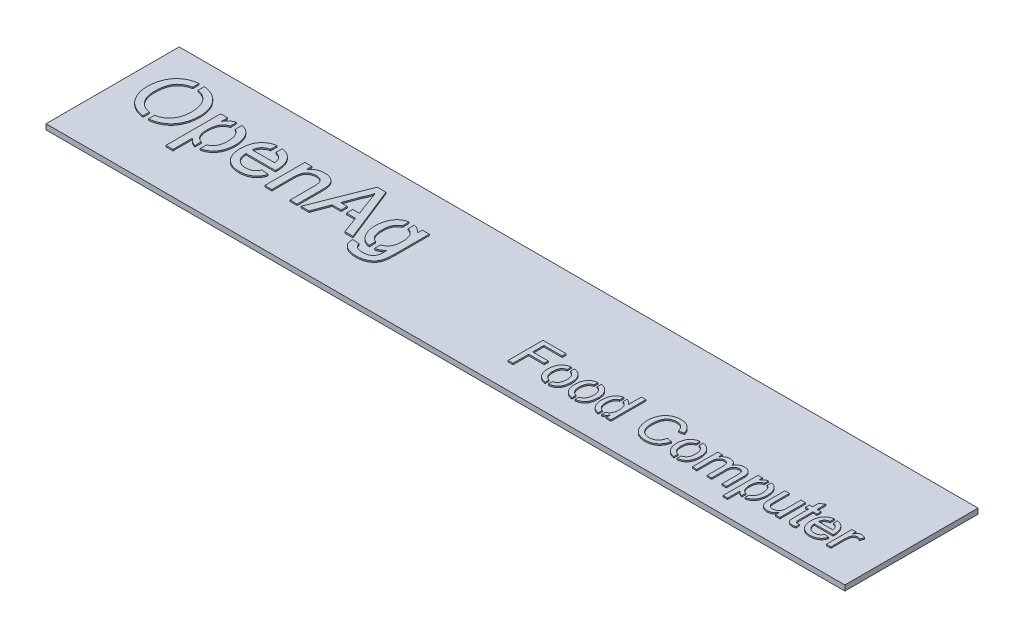
SolidWorks part; units mm, degrees
ref_plane "Front" through (0, 0, 0) normal (0, 0, 1) x (1, 0, 0)
ref_plane "Top" through (0, 0, 0) normal (0, 1, 0) x (1, 0, 0)
ref_plane "Right" through (0, 0, 0) normal (1, 0, 0) x (0, 0, -1)
sketch "Sketch1" plane through (0, 0, 0) normal (0, 1, 0) x (1, 0, 0)
  line L0 (-150, 18.65) -> (150, 18.65) construction
  line L1 (-150, 25) -> (150, 25) construction
  line L2 (-150, 25) -> (-150, -25) construction
  line L3 (-150, -25) -> (150, -25) construction
  line L4 (150, 25) -> (150, -25) construction
  line L5 (-150, 25) -> (150, -25) construction
  line L6 (-150, -25) -> (150, 25) construction
  line L7 (150, -18.65) -> (-150, -18.65) construction
  line L8 (0, 18.65) -> (0, 25) construction
  line L9 (0, -18.65) -> (0, -25) construction
  line L10 (-150, -4.4674) -> (-33.5363, -4.4674) construction
  line L11 (-33.5363, -4.4674) -> (-33.5363, 25) construction
  line L12 (150, -15.7009) -> (1.3927, -15.7009) construction
  line L13 (1.3927, -15.7009) -> (1.3927, -25) construction
  line L14 (-143.65, 25) -> (-143.65, -25) construction
  line L15 (143.65, 25) -> (143.65, -25) construction
  text T0 "OpenAg" font "Arial" height in points 80
  text T1 "Food Computer" font "Arial" height in points 51
  point P0 (0, 0)
  point P24 (1.3927, -15.7009)
  point P25 (0, 0)
  dimension "D1" = 300
  dimension "D2" = 50
  dimension "D3" = 6.35
  dimension "D4" = 6.35
  dimension "D5" = 6.35
extrude "Boss-Extrude1" add sketch "Sketch1" along normal blind 2.5
sketch "Sketch4" plane through (0, 0, 0) normal (0, 1, 0) x (1, 0, 0)
  line L1 (-150, 25) -> (150, 25)
  line L2 (-150, 25) -> (-150, -25)
  line L3 (-150, -25) -> (150, -25)
  line L4 (150, 25) -> (150, -25)
  line L5 (-150, 25) -> (150, -25) construction
  line L6 (-150, -25) -> (150, 25) construction
  point P0 (0, 0)
  dimension "D1" = 50
  dimension "D2" = 300
extrude "Boss-Extrude2" add sketch "Sketch4" along normal blind 2
sketch "Sketch5" plane through (0, 2, 0) normal (0, 1, 0) x (1, 0, 0)
  line L0 (-132.8325, 13.9718) -> (-132.8489, 16.3426) construction
  line L1 (-132.8736, -2.3601) -> (-132.8613, -4.7308) construction
  line L2 (-98.012, 8.4401) -> (-97.9996, 10.8108) construction
  line L3 (-65.0313, 4.2254) -> (-65.0313, 1.8546) construction
  line L4 (-48.2865, -2.0896) -> (-48.2673, -4.4674) construction
  line L6 (-48.3908, 10.8108) -> (-48.3715, 8.43) construction
  line L8 (-113.1461, 10.8108) -> (-113.1461, 8.4271) construction
  line L9 (28.8495, -7.4724) -> (28.8495, -5.961) construction
  line L10 (28.8495, -14.3574) -> (28.8495, -15.8688) construction
  line L11 (38.9253, -7.4724) -> (38.9253, -5.961) construction
  line L12 (38.9253, -14.3574) -> (38.9253, -15.8688) construction
  line L13 (48.5916, -5.961) -> (48.5916, -7.4762) construction
  line L14 (48.7701, -14.3574) -> (48.7701, -15.8615) construction
  line L15 (77.213, -7.4724) -> (77.213, -5.961) construction
  line L16 (77.213, -14.3574) -> (77.213, -15.8688) construction
  line L17 (102.8745, -5.961) -> (102.8745, -7.4806) construction
  line L18 (102.6777, -15.8688) -> (102.6777, -14.3556) construction
  line L19 (127.6361, -7.4724) -> (127.644, -5.961) construction
  line L20 (-113.4548, -4.7308) -> (-113.4548, -2.3572) construction
  line L21 (-68.5381, 4.2254) -> (-61.5246, 4.2254) construction
  line L22 (-69.4106, 1.8546) -> (-60.652, 1.8546) construction
  line L39 (-69.4106, 1.8546) -> (-60.652, 1.8546) construction
  line L70 (-66.0313, 1.8546) -> (-64.0313, 1.8546)
  line L83 (-66.0313, 4.2254) -> (-64.0313, 4.2254)
  line L85 (-131.832, 13.9054) -> (-131.8486, 16.3007)
  line L86 (-133.874, -2.2961) -> (-133.8615, -4.6884)
  line L87 (-114.1461, 10.7192) -> (-114.1461, 8.3626)
  line L88 (-112.4548, -4.6448) -> (-112.4548, -2.1851)
  line L89 (-97.0124, 8.3488) -> (-96.9999, 10.7492)
  line L90 (-66.0313, 4.2254) -> (-66.0313, 1.8546)
  line L91 (-49.2881, -1.897) -> (-49.2678, -4.4011)
  line L92 (-49.3902, 10.7356) -> (-49.3697, 8.2033)
  line L93 (-133.832, 13.9081) -> (-133.8487, 16.3016)
  line L94 (-131.8739, -2.2986) -> (-131.8615, -4.6854)
  line L95 (-112.1461, 10.7335) -> (-112.1461, 8.1741)
  line L96 (-114.4548, -4.6242) -> (-114.4548, -2.2397)
  line L97 (-99.0125, 8.352) -> (-98.9999, 10.7539)
  line L98 (-64.0313, 4.2254) -> (-64.0313, 1.8546)
  line L99 (-47.2871, -2.0156) -> (-47.2679, -4.3821)
  line L100 (-47.39, 10.7215) -> (-47.3709, 8.3625)
  line L101 (29.4495, -7.5363) -> (29.4495, -5.994)
  line L102 (28.2495, -14.2956) -> (28.2495, -15.8367)
  line L103 (38.3253, -14.2956) -> (38.3253, -15.8367)
  line L104 (39.5253, -7.5363) -> (39.5253, -5.994)
  line L105 (47.9916, -6.0055) -> (47.9916, -7.5875)
  line L106 (48.1701, -14.2737) -> (48.1701, -15.8438)
  line L107 (77.813, -7.5363) -> (77.813, -5.994)
  line L108 (76.613, -14.2956) -> (76.613, -15.8367)
  line L109 (102.2745, -6.0122) -> (102.2745, -7.5133)
  line L110 (103.2777, -15.8201) -> (103.2777, -14.2584)
  line L111 (128.2359, -7.5234) -> (128.2438, -5.9957)
  line L112 (28.2495, -7.5343) -> (28.2495, -5.9936)
  line L113 (29.4495, -14.2918) -> (29.4495, -15.8319)
  line L114 (39.5253, -14.2918) -> (39.5253, -15.8319)
  line L115 (38.3253, -7.5343) -> (38.3253, -5.9936)
  line L116 (49.1916, -6.0167) -> (49.1916, -7.5243)
  line L117 (49.3701, -14.2776) -> (49.3701, -15.7769)
  line L118 (76.613, -7.5343) -> (76.613, -5.9936)
  line L119 (77.813, -14.2918) -> (77.813, -15.8319)
  line L120 (103.4745, -6.0047) -> (103.4745, -7.6254)
  line L121 (102.0777, -15.8092) -> (102.0777, -14.2904)
  line L122 (127.0359, -7.5218) -> (127.0438, -5.9931)
  line L123 (-133.8324, 13.9649) -> (-133.8489, 16.3356) construction
  line L124 (-131.8325, 13.9788) -> (-131.8489, 16.3495) construction
  line L125 (-133.8736, -2.3653) -> (-133.8613, -4.736) construction
  line L126 (-131.8736, -2.3548) -> (-131.8613, -4.7256) construction
  line L127 (-114.4548, -4.7308) -> (-114.4548, -2.3572) construction
  line L128 (-112.4548, -4.7308) -> (-112.4548, -2.3572) construction
  line L129 (-112.1461, 10.8108) -> (-112.1461, 8.4271) construction
  line L130 (-114.1461, 10.8108) -> (-114.1461, 8.4271) construction
  line L131 (-99.012, 8.4453) -> (-98.9996, 10.816) construction
  line L132 (-97.012, 8.4348) -> (-96.9997, 10.8056) construction
  line L133 (-49.3907, 10.8027) -> (-49.3715, 8.4219) construction
  line L134 (-47.3908, 10.8189) -> (-47.3715, 8.4381) construction
  line L135 (-49.2865, -2.0977) -> (-49.2672, -4.4755) construction
  line L136 (-47.2865, -2.0815) -> (-47.2673, -4.4593) construction
  line L137 (28.2495, -7.4724) -> (28.2495, -5.961) construction
  line L138 (29.4495, -7.4724) -> (29.4495, -5.961) construction
  line L139 (28.2495, -14.3574) -> (28.2495, -15.8688) construction
  line L140 (29.4495, -14.3574) -> (29.4495, -15.8688) construction
  line L141 (38.3253, -14.3574) -> (38.3253, -15.8688) construction
  line L142 (39.5253, -14.3574) -> (39.5253, -15.8688) construction
  line L143 (38.3253, -7.4724) -> (38.3253, -5.961) construction
  line L144 (39.5253, -7.4724) -> (39.5253, -5.961) construction
  line L145 (47.9916, -5.961) -> (47.9916, -7.4762) construction
  line L146 (49.1916, -5.961) -> (49.1916, -7.4762) construction
  line L147 (48.1701, -14.3574) -> (48.1701, -15.8615) construction
  line L148 (49.3701, -14.3574) -> (49.3701, -15.8615) construction
  line L149 (77.813, -7.4724) -> (77.813, -5.961) construction
  line L150 (76.613, -7.4724) -> (76.613, -5.961) construction
  line L151 (76.613, -14.3574) -> (76.613, -15.8688) construction
  line L152 (77.813, -14.3574) -> (77.813, -15.8688) construction
  line L153 (103.4745, -5.961) -> (103.4745, -7.4806) construction
  line L154 (102.2745, -5.961) -> (102.2745, -7.4806) construction
  line L155 (103.2777, -15.8688) -> (103.2777, -14.3556) construction
  line L156 (102.0777, -15.8688) -> (102.0777, -14.3556) construction
  line L157 (127.0361, -7.4692) -> (127.044, -5.9579) construction
  line L158 (128.2361, -7.4755) -> (128.244, -5.9641) construction
  spline S0 degree 3 poles (46.3089, -10.9201) (46.3108, -10.7758) (46.3146, -10.4972) (46.3448, -10.0946) (46.4017, -9.7227) (46.4719, -9.3786) (46.5693, -9.0651) (46.6874, -8.7819) (46.8265, -8.5279) (46.987, -8.3041) (47.1649, -8.1089) (47.3522, -7.9381) (47.5521, -7.7954) (47.7596, -7.6742) (47.9817, -7.5871) (48.2123, -7.5195) (48.4538, -7.4799) (48.6186, -7.4749) (48.7018, -7.4724) knots 0 0 0 0 0.091711 0.176988 0.256201 0.330636 0.399883 0.464382 0.525315 0.58345 0.638919 0.692818 0.744171 0.79469 0.845044 0.895343 0.947139 1 1 1 1 construction
  spline S1 degree 3 poles (48.5995, -15.8688) (48.7371, -15.8635) (49.0065, -15.8531) (49.3977, -15.7797) (49.7631, -15.6523) (50.1004, -15.4715) (50.415, -15.2439) (50.6984, -14.9606) (50.9617, -14.6323) (51.1051, -14.3832) (51.1788, -14.2551) knots 0 0 0 0 0.128569 0.251669 0.370306 0.48876 0.608091 0.731764 0.86208 1 1 1 1 construction
  spline S2 degree 3 poles (77.213, -5.961) (77.3697, -5.9654) (77.6763, -5.9741) (78.1262, -6.0305) (78.5523, -6.1353) (78.9599, -6.2727) (79.343, -6.4558) (79.7076, -6.6741) (80.0448, -6.9387) (80.3609, -7.2377) (80.6462, -7.5721) (80.8947, -7.9402) (81.1051, -8.339) (81.2789, -8.7686) (81.4123, -9.2295) (81.5052, -9.7206) (81.5647, -10.2408) (81.5708, -10.5981) (81.5739, -10.7811) knots 0 0 0 0 0.064148 0.125517 0.185171 0.243479 0.301291 0.358638 0.417072 0.476329 0.536519 0.596593 0.65777 0.720728 0.785986 0.853812 0.925134 1 1 1 1 construction
  spline S3 degree 3 poles (628.4032, 5968.974) (81.1569, -66.8525) (94.984, -6.0623) (103.1617, -7.5211) (103.3881, -7.585) (103.6035, -7.6817) (103.8118, -7.801) (104.0097, -7.9483) (104.2009, -8.1209) (104.3812, -8.3196) (104.5473, -8.5455) (104.6915, -8.7994) (104.8152, -9.0786) (104.915, -9.3855) (104.9892, -9.7188) (105.0441, -10.0782) (106.3518, -24.5237) (47.0282, -41.4073) (6100.8984, 199.8082) knots -5.190221 -5.190221 -5.190221 -5.190221 0.051984 0.10235 0.152881 0.203408 0.254215 0.307479 0.362207 0.420123 0.480272 0.542695 0.608117 0.676987 0.750486 0.828128 0.91139 10.097658 10.097658 10.097658 10.097658 only from (102.6882, -7.4724) to (105.0838, -10.8677) construction
  spline S4 degree 3 poles (102.62, -14.3574) (102.7032, -14.3549) (102.868, -14.3498) (103.1107, -14.3105) (103.3422, -14.2405) (103.5662, -14.1491) (103.778, -14.0259) (103.9853, -13.8823) (104.1788, -13.7061) (104.3663, -13.5077) (104.5374, -13.2792) (104.6846, -13.0198) (104.8071, -12.7314) (104.9099, -12.4155) (104.9873, -12.0692) (105.0445, -11.6949) (105.079, -11.2908) (105.0822, -11.0121) (105.0838, -10.8677) knots 0 0 0 0 0.052073 0.103097 0.153325 0.203136 0.254125 0.306368 0.360644 0.417574 0.47702 0.538803 0.603778 0.672846 0.746409 0.825605 0.909656 1 1 1 1 construction
  spline S5 degree 3 poles (403.8523, 5985.4848) (-141.4535, -60.469) (-123.7873, 10.3421) (-112.6957, 8.3635) (-112.3405, 8.2633) (-112.0026, 8.1117) (-111.6759, 7.9245) (-111.3655, 7.6935) (-111.0655, 7.4228) (-110.7827, 7.1111) (-110.5222, 6.7568) (-110.2959, 6.3585) (-110.1019, 5.9204) (-109.9454, 5.4391) (-109.829, 4.9163) (-109.7429, 4.3525) (-107.9699, -15.2339) (-177.0738, -37.6224) (5886.4299, 198.9811) knots -4.467052 -4.467052 -4.467052 -4.467052 0.051984 0.10235 0.152881 0.203408 0.254215 0.307479 0.362207 0.420123 0.480272 0.542695 0.608117 0.676987 0.750486 0.828128 0.91139 8.829953 8.829953 8.829953 8.829953 only from (-113.4384, 8.4401) to (-109.6805, 3.1141) construction
  spline S6 degree 3 poles (-528.0011, -5982.1822) (-19.1735, 66.2736) (-37.0644, -3.9917) (-48.8654, -2.0209) (-49.2351, -1.9241) (-49.5851, -1.7808) (-49.9197, -1.5995) (-50.2367, -1.3763) (-50.5355, -1.1138) (-50.8168, -0.8127) (-51.0739, -0.4672) (-51.2911, -0.0693) (-51.4815, 0.3708) (-51.631, 0.8601) (-51.7521, 1.3936) (-51.8293, 1.9764) (-53.646, 21.9982) (17.0267, 45.2598) (-6046.9731, -222.4236) knots -4.668214 -4.668214 -4.668214 -4.668214 0.053891 0.106705 0.157849 0.208129 0.259273 0.311454 0.364536 0.419889 0.477816 0.538174 0.602795 0.671409 0.744769 0.823784 0.90898 8.869625 8.869625 8.869625 8.869625 only from (-48.0821, -2.0966) to (-51.8934, 3.2664) construction
  spline S7 degree 3 poles (-48.0821, -2.0966) (-48.2154, -2.0928) (-48.4794, -2.0853) (-48.8654, -2.0209) (-49.1329, -1.9509) (-49.2703, -1.9034) (-49.2881, -1.897) knots 0 0 0 0 0.053891 0.106705 0.157849 0.165489 0.165489 0.165489 0.165489
  spline S9 degree 3 poles (5952.1205, -190.9815) (-112.0125, 44.4485) (-42.5371, 21.7847) (-44.3168, 1.9251) (-44.4019, 1.3557) (-44.5188, 0.8301) (-44.6767, 0.35) (-44.8636, -0.0871) (-45.0865, -0.4798) (-45.3484, -0.8218) (-45.6326, -1.1207) (-45.9303, -1.385) (-46.2488, -1.6036) (-46.5849, -1.7818) (-46.9358, -1.9211) (-47.3015, -2.0279) (-59.9427, -3.8604) (-76.6366, 61.7596) (285.8876, -5992.3125) knots -7.881366 -7.881366 -7.881366 -7.881366 0.089653 0.173434 0.251626 0.324597 0.392973 0.4577 0.518425 0.576794 0.633062 0.686653 0.739015 0.790385 0.841666 0.892911 0.945592 6.039598 6.039598 6.039598 6.039598 only from (-44.2543, 3.1841) to (-48.0821, -2.0966) construction
  spline S12 degree 3 poles (6125.5858, 253.3517) (63.505, -47.4858) (133.7551, -26.8405) (131.8841, -9.8029) (131.7902, -9.2957) (131.6605, -8.8208) (131.4921, -8.3781) (131.2843, -7.9701) (131.0389, -7.5936) (130.7552, -7.2539) (130.4438, -6.9498) (130.108, -6.6846) (129.7499, -6.4619) (129.3721, -6.2754) (128.9704, -6.1333) (128.5469, -6.0354) (114.6964, -4.0842) (95.8591, -73.9247) (514.9772, 5980.9047) knots -6.719949 -6.719949 -6.719949 -6.719949 0.077348 0.150464 0.219738 0.286329 0.349752 0.411446 0.471642 0.531576 0.590509 0.647833 0.704706 0.761168 0.818371 0.877035 0.937167 6.478203 6.478203 6.478203 6.478203 only from (131.9524, -10.9044) to (127.644, -5.961) construction
  spline S13 degree 3 poles (-187.2019, 5985.2152) (160.0439, -72.4677) (141.3542, -4.1235) (126.7106, -6.0333) (126.276, -6.1394) (125.8629, -6.2836) (125.4738, -6.4713) (125.105, -6.6973) (124.7639, -6.9712) (124.4436, -7.2792) (124.1541, -7.6255) (123.9041, -8.0095) (123.6912, -8.4253) (123.5167, -8.8754) (123.385, -9.3595) (123.288, -9.8753) (121.4276, -27.2928) (191.4167, -48.0704) (-5871.0303, 233.0369) knots -5.657995 -5.657995 -5.657995 -5.657995 0.063518 0.124379 0.183252 0.24061 0.297531 0.35421 0.411724 0.470579 0.530161 0.590272 0.651841 0.715077 0.781286 0.850452 0.922981 7.71573 7.71573 7.71573 7.71573 only from (127.644, -5.961) to (123.2201, -10.9962) construction
  spline S16 degree 3 poles (-4563.4852, -3789.0222) (138.3162, 44.6052) (92.8765, -6.9261) (100.673, -15.0449) (100.9465, -15.2797) (101.2471, -15.4863) (101.5722, -15.6608) (101.9236, -15.7789) (112.4638, -18.0058) (131.2339, 58.278) (-501.2518, -5985.0208) knots -11.110272 -11.110272 -11.110272 -11.110272 0.121777 0.242565 0.364944 0.489682 0.614851 0.740669 0.867437 11.580571 11.580571 11.580571 11.580571 only from (100.2139, -14.4991) to (102.6777, -15.8688) construction
  spline S17 degree 3 poles (726.9002, -5982.7171) (67.8423, 65.7164) (90.5586, -18.704) (103.7443, -15.7258) (104.2586, -15.5277) (104.6701, -15.3041) (104.9862, -15.0907) (105.2103, -14.9081) (105.4197, -14.7081) (105.6173, -14.4941) (105.7966, -14.2604) (105.9613, -14.0108) (106.1148, -13.7454) (106.2959, -13.3653) (106.4849, -12.8602) (106.647, -12.2198) (109.3013, 5.7891) (26.597, 29.5938) (6094.7535, -380.3164) knots -5.345356 -5.345356 -5.345356 -5.345356 0.074112 0.148308 0.223537 0.301842 0.341738 0.381405 0.421384 0.461647 0.501941 0.543242 0.58544 0.62887 0.717498 0.808361 0.902078 8.239064 8.239064 8.239064 8.239064 only from (102.6777, -15.8688) to (106.7631, -10.8441) construction
  spline S18 degree 3 poles (6094.1401, 369.1544) (29.8554, -50.3593) (109.1382, -27.1127) (106.6571, -9.5462) (106.5185, -8.9316) (106.3479, -8.4445) (106.1873, -8.0732) (106.0509, -7.8127) (105.9039, -7.566) (105.7409, -7.3368) (105.5616, -7.1256) (105.3735, -6.926) (105.1663, -6.7484) (104.95, -6.583) (104.7217, -6.4351) (104.4825, -6.3106) (104.2367, -6.2013) (103.9817, -6.1117) (103.7165, -6.0436) (103.4426, -5.9973) (92.2537, -4.8089) (78.1055, -58.1135) (405.5113, 5985.8362) knots -7.30323 -7.30323 -7.30323 -7.30323 0.09481 0.186622 0.276167 0.364139 0.407057 0.449256 0.489899 0.529896 0.569491 0.608415 0.647156 0.686169 0.724905 0.763423 0.801475 0.839957 0.879004 0.918519 0.95879 5.690354 5.690354 5.690354 5.690354 only from (106.7631, -10.8441) to (102.8745, -5.961) construction
  spline S19 degree 3 poles (-393.7538, 5972.9607) (132.3713, -80.5925) (113.7585, -3.7568) (102.0456, -6.0542) (101.6766, -6.1899) (101.3371, -6.376) (101.0269, -6.6188) (100.7337, -6.9096) (91.7621, -18.3166) (141.3204, -69.0158) (-4897.8693, 3310.9621) knots -10.362563 -10.362563 -10.362563 -10.362563 0.130672 0.253147 0.37019 0.484823 0.60151 0.725044 0.857266 13.683902 13.683902 13.683902 13.683902 only from (102.8745, -5.961) to (100.2139, -7.6482) construction
  spline S20 degree 3 poles (-5921.0626, -268.221) (141.2182, 26.2328) (71.0403, 5.3336) (72.9098, -12.0365) (73.0032, -12.5508) (73.1334, -13.0311) (73.3039, -13.4761) (73.5125, -13.8858) (73.7562, -14.2619) (74.0418, -14.5968) (74.3541, -14.8976) (74.6932, -15.1575) (75.0563, -15.3784) (75.4438, -15.5553) (75.8524, -15.6994) (76.2854, -15.7983) (91.1059, -17.6728) (110.1112, 49.3805) (-255.8591, -6006.1386) knots -6.777455 -6.777455 -6.777455 -6.777455 0.077929 0.151663 0.221236 0.287458 0.350988 0.412027 0.471582 0.530342 0.588161 0.645214 0.701415 0.758242 0.81583 0.874895 0.936082 6.797587 6.797587 6.797587 6.797587 only from (72.8416, -10.9149) to (77.213, -15.8688) construction
  spline S21 degree 3 poles (595.2808, -5992.7538) (40.5928, 65.1916) (63.4653, -18.5907) (78.3876, -15.7368) (78.9434, -15.5549) (79.3822, -15.3426) (79.7147, -15.14) (79.9502, -14.9731) (80.1699, -14.7901) (80.3741, -14.5936) (80.5644, -14.383) (80.738, -14.1565) (80.8948, -13.9147) (81.0388, -13.6579) (81.165, -13.3806) (81.2747, -13.0804) (81.3694, -12.7572) (81.4453, -12.4091) (81.5016, -12.0365) (81.543, -11.6398) (82.6438, 5.2779) (27.8566, 23.7921) (6079.283, -146.7621) knots -5.741185 -5.741185 -5.741185 -5.741185 0.078868 0.155793 0.232112 0.309167 0.347597 0.385726 0.422992 0.460352 0.497512 0.53494 0.572862 0.611192 0.651053 0.692999 0.737248 0.783909 0.833521 0.885947 0.941297 7.52267 7.52267 7.52267 7.52267 only from (77.213, -15.8688) to (81.5739, -10.7811) construction
  spline S22 degree 3 poles (6074.1241, 275.4588) (13.2907, -46.2945) (83.3777, -26.0847) (81.5052, -9.7206) (81.4123, -9.2295) (81.2789, -8.7686) (81.1051, -8.339) (80.8947, -7.9402) (80.6462, -7.5721) (80.3609, -7.2377) (80.0448, -6.9387) (79.7076, -6.6741) (79.343, -6.4558) (78.9599, -6.2727) (78.5523, -6.1353) (78.1262, -6.0305) (63.3575, -4.1788) (44.9946, -70.3699) (363.3348, 5986.3574) knots -6.518201 -6.518201 -6.518201 -6.518201 0.074866 0.146188 0.214014 0.279272 0.34223 0.403407 0.463481 0.523671 0.582928 0.641362 0.698709 0.756521 0.814829 0.874483 0.935852 6.892896 6.892896 6.892896 6.892896 only from (81.5739, -10.7811) to (77.213, -5.961) construction
  spline S23 degree 3 poles (-262.8938, 5984.0261) (107.1525, -70.9992) (89.6713, -4.3209) (76.3838, -6.0211) (75.9909, -6.1012) (75.6145, -6.2166) (75.2558, -6.3676) (74.9137, -6.5497) (64.4868, -13.275) (95.611, -75.037) (-3560.2281, 4765.9981) knots -12.21018 -12.21018 -12.21018 -12.21018 0.133569 0.262234 0.387629 0.510902 0.632401 0.753664 0.875698 12.29516 12.29516 12.29516 12.29516 only from (77.213, -5.961) to (74.2821, -7.0132) construction
  spline S25 degree 3 poles (4819.6723, 3633.4034) (6.3522, -69.0691) (58.3062, -15.0445) (50.7051, -6.8411) (50.4212, -6.5853) (50.104, -6.3673) (49.7628, -6.1816) (49.3921, -6.0543) (38.038, -3.7854) (19.0422, -78.9676) (614.4013, 5966.8786) knots -10.371374 -10.371374 -10.371374 -10.371374 0.123897 0.245576 0.36732 0.491423 0.615422 0.740391 0.867456 11.723716 11.723716 11.723716 11.723716 only from (51.1788, -7.4409) to (48.5916, -5.961) construction
  spline S26 degree 3 poles (-261.669, 5985.3162) (73.2134, -58.1482) (59.1067, -4.8082) (48.0288, -5.9973) (47.7566, -6.0436) (47.4913, -6.1131) (47.2323, -6.1987) (46.9803, -6.3045) (46.7366, -6.4317) (46.4983, -6.5739) (46.2731, -6.7378) (46.0589, -6.9155) (45.8626, -7.1141) (45.6783, -7.3263) (45.5092, -7.5558) (45.3572, -7.8041) (45.2186, -8.0692) (45.0497, -8.4455) (44.8799, -8.9459) (44.7376, -9.5767) (42.2063, -27.5231) (123.32, -51.0866) (-5943.6348, 354.2385) knots -4.560064 -4.560064 -4.560064 -4.560064 0.040095 0.079269 0.117704 0.156042 0.194402 0.232292 0.270763 0.309849 0.348821 0.387697 0.426687 0.46604 0.505741 0.546343 0.588271 0.63138 0.719612 0.809763 0.902871 8.320902 8.320902 8.320902 8.320902 only from (48.5916, -5.961) to (44.6296, -10.9228) construction
  spline S27 degree 3 poles (-5945.4063, -344.5468) (123.1011, 29.5279) (42.1522, 6.0285) (44.7414, -12.2874) (44.9032, -12.914) (45.0861, -13.4053) (45.2659, -13.7715) (45.4129, -14.0293) (45.5729, -14.2715) (45.7468, -14.4966) (45.9303, -14.7094) (46.1316, -14.9016) (46.3401, -15.0858) (46.5669, -15.2455) (46.7989, -15.3945) (47.0409, -15.5183) (47.2858, -15.6291) (47.5391, -15.7131) (47.7954, -15.7871) (48.0595, -15.832) (58.6053, -17.0273) (72.5498, 36.3959) (-302.7834, -6004.8794) knots -7.522855 -7.522855 -7.522855 -7.522855 0.099676 0.19464 0.285231 0.373096 0.415974 0.457756 0.498618 0.538747 0.578098 0.617364 0.656471 0.695717 0.734642 0.773054 0.810678 0.848255 0.885884 0.923497 0.961473 5.373852 5.373852 5.373852 5.373852 only from (44.6296, -10.9228) to (48.5995, -15.8688) construction
  spline S28 degree 3 poles (551.2145, -5994.1482) (19.3376, 54.898) (37.6768, -17.9776) (49.3977, -15.7797) (49.7631, -15.6523) (50.1004, -15.4715) (50.415, -15.2439) (50.6984, -14.9606) (58.3827, -5.3775) (0.4983, 47.5826) (5068.6876, -3303.2011) knots -10.725352 -10.725352 -10.725352 -10.725352 0.128569 0.251669 0.370306 0.48876 0.608091 0.731764 0.86208 12.047701 12.047701 12.047701 12.047701 only from (48.5995, -15.8688) to (51.1788, -14.2551) construction
  spline S29 degree 3 poles (-5959.3503, -268.221) (102.9305, 26.2328) (32.7526, 5.3336) (34.6221, -12.0365) (34.7155, -12.5508) (34.8457, -13.0311) (35.0162, -13.4761) (35.2248, -13.8858) (35.4685, -14.2619) (35.7541, -14.5968) (36.0664, -14.8976) (36.4055, -15.1575) (36.7685, -15.3784) (37.1561, -15.5553) (37.5647, -15.6994) (37.9977, -15.7983) (52.8182, -17.6728) (71.8235, 49.3805) (-294.1468, -6006.1386) knots -6.777455 -6.777455 -6.777455 -6.777455 0.077929 0.151663 0.221236 0.287458 0.350988 0.412027 0.471582 0.530342 0.588161 0.645214 0.701415 0.758242 0.81583 0.874895 0.936082 6.797587 6.797587 6.797587 6.797587 only from (34.5539, -10.9149) to (38.9253, -15.8688) construction
  spline S30 degree 3 poles (556.9931, -5992.7538) (2.3051, 65.1916) (25.1776, -18.5907) (40.0999, -15.7368) (40.6557, -15.5549) (41.0945, -15.3426) (41.427, -15.14) (41.6625, -14.9731) (41.8822, -14.7901) (42.0864, -14.5936) (42.2767, -14.383) (42.4503, -14.1565) (42.6071, -13.9147) (42.7511, -13.6579) (42.8772, -13.3806) (42.987, -13.0804) (43.0817, -12.7572) (43.1576, -12.4091) (43.2139, -12.0365) (43.2553, -11.6398) (44.3561, 5.2779) (-10.4311, 23.7921) (6040.9953, -146.7621) knots -5.741185 -5.741185 -5.741185 -5.741185 0.078868 0.155793 0.232112 0.309167 0.347597 0.385726 0.422992 0.460352 0.497512 0.53494 0.572862 0.611192 0.651053 0.692999 0.737248 0.783909 0.833521 0.885947 0.941297 7.52267 7.52267 7.52267 7.52267 only from (38.9253, -15.8688) to (43.2861, -10.7811) construction
  spline S31 degree 3 poles (6035.8364, 275.4588) (-24.997, -46.2945) (45.09, -26.0847) (43.2175, -9.7206) (43.1246, -9.2295) (42.9912, -8.7686) (42.8174, -8.339) (42.607, -7.9402) (42.3585, -7.5721) (42.0732, -7.2377) (41.7571, -6.9387) (41.4199, -6.6741) (41.0553, -6.4558) (40.6722, -6.2727) (40.2646, -6.1353) (39.8385, -6.0305) (25.0698, -4.1788) (6.7069, -70.3699) (325.0471, 5986.3574) knots -6.518201 -6.518201 -6.518201 -6.518201 0.074866 0.146188 0.214014 0.279272 0.34223 0.403407 0.463481 0.523671 0.582928 0.641362 0.698709 0.756521 0.814829 0.874483 0.935852 6.892896 6.892896 6.892896 6.892896 only from (43.2861, -10.7811) to (38.9253, -5.961) construction
  spline S32 degree 3 poles (-301.1815, 5984.0261) (68.8648, -70.9992) (51.3836, -4.3209) (38.096, -6.0211) (37.7032, -6.1012) (37.3268, -6.2166) (36.9681, -6.3676) (36.626, -6.5497) (26.1991, -13.275) (57.3233, -75.037) (-3598.5158, 4765.9981) knots -12.21018 -12.21018 -12.21018 -12.21018 0.133569 0.262234 0.387629 0.510902 0.632401 0.753664 0.875698 12.29516 12.29516 12.29516 12.29516 only from (38.9253, -5.961) to (35.9944, -7.0132) construction
  spline S34 degree 3 poles (-5969.426, -268.221) (92.8548, 26.2328) (22.6769, 5.3336) (24.5463, -12.0365) (24.6398, -12.5508) (24.77, -13.0311) (24.9405, -13.4761) (25.1491, -13.8858) (25.3928, -14.2619) (25.6784, -14.5968) (25.9906, -14.8976) (26.3298, -15.1575) (26.6928, -15.3784) (27.0804, -15.5553) (27.4889, -15.6994) (27.922, -15.7983) (42.7425, -17.6728) (61.7478, 49.3805) (-304.2225, -6006.1386) knots -6.777455 -6.777455 -6.777455 -6.777455 0.077929 0.151663 0.221236 0.287458 0.350988 0.412027 0.471582 0.530342 0.588161 0.645214 0.701415 0.758242 0.81583 0.874895 0.936082 6.797587 6.797587 6.797587 6.797587 only from (24.4782, -10.9149) to (28.8495, -15.8688) construction
  spline S35 degree 3 poles (546.9174, -5992.7538) (-7.7706, 65.1916) (15.1019, -18.5907) (30.0242, -15.7368) (30.58, -15.5549) (31.0188, -15.3426) (31.3513, -15.14) (31.5868, -14.9731) (31.8065, -14.7901) (32.0107, -14.5936) (32.201, -14.383) (32.3746, -14.1565) (32.5314, -13.9147) (32.6754, -13.6579) (32.8015, -13.3806) (32.9113, -13.0804) (33.006, -12.7572) (33.0819, -12.4091) (33.1382, -12.0365) (33.1796, -11.6398) (34.2804, 5.2779) (-20.5068, 23.7921) (6030.9196, -146.7621) knots -5.741185 -5.741185 -5.741185 -5.741185 0.078868 0.155793 0.232112 0.309167 0.347597 0.385726 0.422992 0.460352 0.497512 0.53494 0.572862 0.611192 0.651053 0.692999 0.737248 0.783909 0.833521 0.885947 0.941297 7.52267 7.52267 7.52267 7.52267 only from (28.8495, -15.8688) to (33.2104, -10.7811) construction
  spline S36 degree 3 poles (6025.7607, 275.4588) (-35.0728, -46.2945) (35.0143, -26.0847) (33.1418, -9.7206) (33.0488, -9.2295) (32.9155, -8.7686) (32.7417, -8.339) (32.5313, -7.9402) (32.2828, -7.5721) (31.9975, -7.2377) (31.6814, -6.9387) (31.3442, -6.6741) (30.9796, -6.4558) (30.5965, -6.2727) (30.1889, -6.1353) (29.7628, -6.0305) (14.994, -4.1788) (-3.3688, -70.3699) (314.9713, 5986.3574) knots -6.518201 -6.518201 -6.518201 -6.518201 0.074866 0.146188 0.214014 0.279272 0.34223 0.403407 0.463481 0.523671 0.582928 0.641362 0.698709 0.756521 0.814829 0.874483 0.935852 6.892896 6.892896 6.892896 6.892896 only from (33.2104, -10.7811) to (28.8495, -5.961) construction
  spline S37 degree 3 poles (-311.2572, 5984.0261) (58.7891, -70.9992) (41.3078, -4.3209) (28.0203, -6.0211) (27.6275, -6.1012) (27.2511, -6.2166) (26.8924, -6.3676) (26.5503, -6.5497) (16.1234, -13.275) (47.2476, -75.037) (-3608.5916, 4765.9981) knots -12.21018 -12.21018 -12.21018 -12.21018 0.133569 0.262234 0.387629 0.510902 0.632401 0.753664 0.875698 12.29516 12.29516 12.29516 12.29516 only from (28.8495, -5.961) to (25.9187, -7.0132) construction
  spline S41 degree 3 poles (4436.1979, 3998.4006) (-83.8595, -70.2196) (-32.9355, -1.8781) (-45.1102, 9.6278) (-45.5861, 9.9966) (-46.0949, 10.2929) (-46.6294, 10.5259) (-47.1918, 10.6916) (-62.8825, 13.3727) (-85.3897, -68.4678) (401.8549, 5993.2335) knots -10.012139 -10.012139 -10.012139 -10.012139 0.13448 0.263121 0.386769 0.508467 0.628549 0.748776 0.872589 10.502746 10.502746 10.502746 10.502746 only from (-44.2543, 8.7035) to (-48.3908, 10.8108) construction
  spline S42 degree 3 poles (-283.4705, 6005.6008) (-14.9166, -48.2904) (-33.4933, 12.3314) (-49.2974, 10.7556) (-49.7303, 10.6763) (-50.1493, 10.5702) (-50.5519, 10.4291) (-50.9414, 10.2614) (-51.3124, 10.0566) (-51.6706, 9.8283) (-52.0078, 9.5676) (-52.3256, 9.283) (-52.624, 8.973) (-52.8993, 8.6348) (-53.1542, 8.2703) (-53.3943, 7.8848) (-53.6086, 7.4698) (-53.8652, 6.8814) (-54.1339, 6.1081) (-54.3577, 5.1365) (-57.787, -18.5472) (36.1481, -48.9504) (-6042.5874, 367.9372) knots -4.175355 -4.175355 -4.175355 -4.175355 0.041658 0.08238 0.122043 0.16081 0.199367 0.237487 0.275577 0.314036 0.352473 0.390905 0.42955 0.468911 0.508924 0.549981 0.591877 0.635318 0.723835 0.813185 0.905126 7.19359 7.19359 7.19359 7.19359 only from (-48.3908, 10.8108) to (-54.5276, 3.0853) construction
  spline S43 degree 3 poles (-6047.4116, -275.5088) (20.5797, 47.2973) (-56.7365, 22.3139) (-54.4332, 1.5931) (-54.309, 0.8821) (-54.1236, 0.2014) (-53.9015, -0.4571) (-53.6141, -1.0831) (-53.28, -1.682) (-52.8995, -2.2494) (-52.4737, -2.7695) (-51.9986, -3.2244) (-51.4814, -3.6111) (-50.9184, -3.9236) (-50.315, -4.1705) (-49.6685, -4.3396) (-32.227, -7.1965) (-7.7253, 80.2175) (-480.0398, -5988.0054) knots -5.472788 -5.472788 -5.472788 -5.472788 0.069202 0.136501 0.201843 0.265687 0.328589 0.390998 0.453094 0.515311 0.576919 0.635888 0.694137 0.752384 0.810911 0.871312 0.934131 5.614027 5.614027 5.614027 5.614027 only from (-54.5276, 3.0853) to (-48.2673, -4.4674) construction
  spline S44 degree 3 poles (368.7788, -5989.3058) (-84.5215, 71.8604) (-62.7746, -6.8225) (-47.1168, -4.3625) (-46.5741, -4.2189) (-46.0564, -4.0155) (-45.5639, -3.7559) (-45.1002, -3.4334) (-32.779, 6.9373) (-77.5663, 75.3817) (4185.5392, -4257.2663) knots -10.018728 -10.018728 -10.018728 -10.018728 0.129176 0.254227 0.376567 0.497703 0.619189 0.741818 0.86855 11.185044 11.185044 11.185044 11.185044 only from (-48.2673, -4.4674) to (-44.2543, -2.6235) construction
  spline S52 degree 3 poles (5902.9923, 249.9182) (-170.6747, -45.6092) (-88.8096, -18.3354) (-91.3485, 4.7843) (-91.4958, 5.58) (-91.6992, 6.3248) (-91.9635, 7.0192) (-92.2894, 7.6593) (-92.6744, 8.2499) (-93.1194, 8.7827) (-93.6078, 9.2597) (-94.1345, 9.6758) (-94.6962, 10.025) (-95.2889, 10.3177) (-95.919, 10.5406) (-96.5833, 10.6941) (-115.3795, 13.3421) (-139.9543, -68.0311) (275.1649, 5998.4052) knots -5.783629 -5.783629 -5.783629 -5.783629 0.077348 0.150464 0.219738 0.286329 0.349752 0.411446 0.471642 0.531576 0.590509 0.647833 0.704706 0.761168 0.818371 0.877035 0.937167 5.714912 5.714912 5.714912 5.714912 only from (-91.2413, 3.0565) to (-97.9996, 10.8108) construction
  spline S53 degree 3 poles (-397.8596, 6002.41) (-55.0489, -66.3262) (-79.5939, 13.2889) (-99.4638, 10.6975) (-100.1455, 10.5309) (-100.7935, 10.3047) (-101.4039, 10.0104) (-101.9825, 9.6558) (-102.5174, 9.2262) (-103.0199, 8.7431) (-103.474, 8.1998) (-103.8662, 7.5975) (-104.2002, 6.9452) (-104.4739, 6.2392) (-104.6804, 5.4799) (-104.8326, 4.6708) (-107.3571, -18.9641) (-25.7975, -46.4619) (-6099.909, 229.1726) knots -4.869564 -4.869564 -4.869564 -4.869564 0.063518 0.124379 0.183252 0.24061 0.297531 0.35421 0.411724 0.470579 0.530161 0.590272 0.651841 0.715077 0.781286 0.850452 0.922981 6.780035 6.780035 6.780035 6.780035 only from (-97.9996, 10.8108) to (-104.939, 2.9124) construction
  spline S56 degree 3 poles (-4788.0818, -3768.1426) (-75.4392, 69.355) (-127.1795, 7.579) (-116.5996, -3.4385) (-116.1705, -3.8068) (-115.699, -4.1309) (-115.189, -4.4045) (-114.6377, -4.5898) (-100.3267, -7.6134) (-76.4264, 81.31) (-706.5653, -5974.8432) knots -9.562267 -9.562267 -9.562267 -9.562267 0.121777 0.242565 0.364944 0.489682 0.614851 0.740669 0.867437 10.106491 10.106491 10.106491 10.106491 only from (-117.3197, -2.5823) to (-113.4548, -4.7308) construction
  spline S57 degree 3 poles (497.2721, -5972.7526) (-158.7176, 89.8612) (-129.6992, -8.5535) (-111.7819, -4.5065) (-110.9751, -4.1957) (-110.3295, -3.8451) (-109.8336, -3.5103) (-109.4822, -3.2239) (-109.1537, -2.9101) (-108.8438, -2.5744) (-108.5625, -2.2078) (-108.3042, -1.8163) (-108.0633, -1.3999) (-107.7792, -0.8038) (-107.4828, -0.0114) (-107.2285, 0.9931) (-103.6233, 25.4542) (-200.045, 56.62) (5881.8403, -347.9924) knots -4.600632 -4.600632 -4.600632 -4.600632 0.074112 0.148308 0.223537 0.301842 0.341738 0.381405 0.421384 0.461647 0.501941 0.543242 0.58544 0.62887 0.717498 0.808361 0.902078 7.230464 7.230464 7.230464 7.230464 only from (-113.4548, -4.7308) to (-107.0464, 3.1511) construction
  spline S58 degree 3 poles (5881.3375, 365.2643) (-196.262, -49.0964) (-103.8433, -18.6692) (-107.2126, 5.187) (-107.4301, 6.1511) (-107.6977, 6.9152) (-107.9496, 7.4976) (-108.1636, 7.9062) (-108.3942, 8.2931) (-108.6499, 8.6527) (-108.9311, 8.984) (-109.2262, 9.2971) (-109.5513, 9.5757) (-109.8905, 9.8352) (-110.2486, 10.0671) (-110.6238, 10.2624) (-111.0093, 10.4338) (-111.4094, 10.5745) (-111.8254, 10.6812) (-112.2551, 10.7539) (-127.4223, 12.3648) (-146.0104, -49.6972) (178.0013, 6003.2113) knots -6.285731 -6.285731 -6.285731 -6.285731 0.09481 0.186622 0.276167 0.364139 0.407057 0.449256 0.489899 0.529896 0.569491 0.608415 0.647156 0.686169 0.724905 0.763423 0.801475 0.839957 0.879004 0.918519 0.95879 5.036833 5.036833 5.036833 5.036833 only from (-107.0464, 3.1511) to (-113.1461, 10.8108) construction
  spline S59 degree 3 poles (-597.7572, 5990.4786) (-74.6148, -75.768) (-98.5449, 13.7836) (-114.4464, 10.6646) (-115.0253, 10.4517) (-115.5578, 10.1598) (-116.0444, 9.7789) (-116.5044, 9.3229) (-128.6762, -6.1531) (-72.3381, -67.5555) (-5123.4311, 3314.4143) knots -8.918717 -8.918717 -8.918717 -8.918717 0.130672 0.253147 0.37019 0.484823 0.60151 0.725044 0.857266 11.916527 11.916527 11.916527 11.916527 only from (-113.1461, 10.8108) to (-117.3197, 8.1643) construction
  spline S60 degree 3 poles (-6137.4166, -226.8116) (-73.0424, 46.804) (-144.4196, 23.8487) (-142.5378, 4.2126) (-142.4505, 3.5635) (-142.3207, 2.9221) (-142.1578, 2.2894) (-141.9533, 1.6668) (-141.7206, 1.0506) (-141.4444, 0.4498) (-141.1386, -0.1357) (-140.7927, -0.6886) (-140.4168, -1.2142) (-139.9987, -1.7006) (-139.555, -2.1659) (-139.0716, -2.5931) (-138.556, -2.9894) (-138.0086, -3.3511) (-137.4347, -3.6763) (-136.8362, -3.9551) (-136.2206, -4.1953) (-135.5856, -4.3938) (-134.9306, -4.5459) (-134.2565, -4.6513) (-113.8032, -6.695) (-89.8555, 66.0048) (-371.7254, -5999.2713) knots -3.606633 -3.606633 -3.606633 -3.606633 0.042093 0.083554 0.124992 0.166052 0.207381 0.248618 0.290057 0.332021 0.373735 0.415036 0.455409 0.495952 0.536368 0.57703 0.617971 0.659396 0.701152 0.742753 0.784285 0.826186 0.868591 0.911466 0.955303 4.756323 4.756323 4.756323 4.756323 only from (-142.6077, 5.5342) to (-132.8613, -4.7308) construction
  spline S61 degree 3 poles (64.9155, -6000.8085) (-175.8734, 59.6239) (-152.3571, -6.5182) (-131.558, -4.6601) (-130.9221, -4.5596) (-130.2959, -4.4254) (-129.6812, -4.2478) (-129.0797, -4.0287) (-128.4894, -3.7717) (-127.9098, -3.482) (-127.3523, -3.1516) (-126.827, -2.7776) (-126.3321, -2.3703) (-125.8696, -1.9258) (-125.445, -1.4399) (-125.0485, -0.9213) (-124.6862, -0.3636) (-124.3577, 0.2279) (-124.0673, 0.849) (-123.8103, 1.4913) (-123.5977, 2.1564) (-123.4189, 2.8401) (-123.2854, 3.5446) (-123.1848, 4.2683) (-121.3303, 28.4115) (-187.6092, 54.7725) (5874.1201, -140.3886) knots -3.765528 -3.765528 -3.765528 -3.765528 0.040917 0.081206 0.121044 0.160801 0.20044 0.240141 0.27998 0.320332 0.360792 0.400579 0.440342 0.480112 0.519955 0.560443 0.601634 0.64374 0.686389 0.729297 0.772543 0.816374 0.860888 0.906038 0.95244 5.368639 5.368639 5.368639 5.368639 only from (-132.8613, -4.7308) to (-123.1148, 5.773) construction
  spline S62 degree 3 poles (5874.9614, 118.4049) (-184.0079, -44.6316) (-121.4177, -17.8118) (-123.1804, 7.2543) (-123.2785, 7.9679) (-123.4016, 8.6632) (-123.5733, 9.3372) (-123.7784, 9.9898) (-124.0173, 10.6247) (-124.2967, 11.2343) (-124.6093, 11.8213) (-124.9577, 12.3764) (-125.3432, 12.8952) (-125.7548, 13.3868) (-126.2094, 13.8363) (-126.6919, 14.2589) (-127.2087, 14.6475) (-127.7586, 14.9994) (-128.3327, 15.3139) (-128.9243, 15.5949) (-129.5373, 15.8216) (-130.1663, 16.0136) (-130.8117, 16.16) (-131.4752, 16.2693) (-152.8038, 18.186) (-176.7873, -50.0965) (50.7765, 6012.6763) knots -4.52858 -4.52858 -4.52858 -4.52858 0.046666 0.092161 0.136649 0.180448 0.223293 0.265781 0.307491 0.349241 0.390297 0.430963 0.470884 0.510312 0.549967 0.589534 0.629402 0.66999 0.710719 0.750975 0.79155 0.832033 0.873092 0.914413 0.956901 4.847467 4.847467 4.847467 4.847467 only from (-123.1148, 5.773) to (-132.8489, 16.3426) construction
  spline S63 degree 3 poles (-482.6678, 6005.2889) (-80.4525, -73.383) (-110.8834, 19.5492) (-134.896, 16.1771) (-135.855, 15.9579) (-136.7652, 15.6448) (-137.6238, 15.2369) (-138.4346, 14.743) (-139.19, 14.1508) (-139.8995, 13.4841) (-140.5347, 12.7299) (-141.0962, 11.908) (-141.5612, 11.0105) (-141.9438, 10.0477) (-142.2455, 9.0172) (-142.4566, 7.9176) (-145.6513, -20.8017) (-54.4, -54.1889) (-6136.9339, 242.2932) knots -4.234899 -4.234899 -4.234899 -4.234899 0.064217 0.125675 0.185372 0.243705 0.301102 0.358698 0.416748 0.476136 0.536238 0.596504 0.657597 0.72047 0.7855 0.853425 0.924774 6.056307 6.056307 6.056307 6.056307 only from (-132.8489, 16.3426) to (-142.6077, 5.5342) construction
  spline S67 degree 3 poles (128.2438, -5.9957) (128.1988, -5.9904) (127.9994, -5.9701) (127.799, -5.965) (127.644, -5.961) knots 0.918773 0.918773 0.918773 0.918773 0.937167 1 1 1 1
  spline S68 degree 3 poles (127.644, -5.961) (127.4838, -5.9652) (127.2834, -5.9704) (127.0838, -5.9889) (127.0438, -5.9931) knots 0 0 0 0 0.063518 0.079441 0.079441 0.079441 0.079441
  spline S71 degree 3 poles (102.0777, -15.8092) (102.1478, -15.8243) (102.3463, -15.8587) (102.5479, -15.8648) (102.6777, -15.8688) knots 0.794269 0.794269 0.794269 0.794269 0.867437 1 1 1 1
  spline S72 degree 3 poles (102.6777, -15.8688) (102.8568, -15.861) (103.0576, -15.8522) (103.2562, -15.8234) (103.2777, -15.8201) knots 0 0 0 0 0.074112 0.083145 0.083145 0.083145 0.083145
  spline S73 degree 3 poles (103.4745, -6.0047) (103.4643, -6.0032) (103.3609, -5.9886) (103.1612, -5.9674) (102.9708, -5.9631) (102.8745, -5.961) knots 0.914109 0.914109 0.914109 0.914109 0.918519 0.95879 1 1 1 1
  spline S74 degree 3 poles (102.8745, -5.961) (102.7299, -5.9658) (102.5289, -5.9724) (102.33, -6.0021) (102.2745, -6.0122) knots 0 0 0 0 0.130672 0.181538 0.181538 0.181538 0.181538
  spline S75 degree 3 poles (76.613, -15.8367) (76.6537, -15.8409) (76.8533, -15.859) (77.0536, -15.8645) (77.213, -15.8688) knots 0.919642 0.919642 0.919642 0.919642 0.936082 1 1 1 1
  spline S76 degree 3 poles (77.213, -15.8688) (77.4129, -15.8617) (77.6133, -15.8546) (77.8124, -15.8319) (77.813, -15.8319) knots 0 0 0 0 0.078868 0.0791 0.0791 0.0791 0.0791
  spline S77 degree 3 poles (77.813, -5.994) (77.7696, -5.9894) (77.57, -5.9711) (77.3697, -5.9654) (77.213, -5.961) knots 0.918003 0.918003 0.918003 0.918003 0.935852 1 1 1 1
  spline S78 degree 3 poles (77.213, -5.961) (77.0711, -5.9636) (76.8706, -5.9674) (76.6712, -5.9867) (76.613, -5.9936) knots 0 0 0 0 0.133569 0.188756 0.188756 0.188756 0.188756
  spline S80 degree 3 poles (49.1916, -6.0167) (49.1293, -6.0046) (48.9305, -5.9733) (48.7293, -5.966) (48.5916, -5.961) knots 0.806337 0.806337 0.806337 0.806337 0.867456 1 1 1 1
  spline S81 degree 3 poles (48.5916, -5.961) (48.4962, -5.9631) (48.3076, -5.9674) (48.1079, -5.9888) (48.0036, -6.0037) (47.9916, -6.0055) knots 0 0 0 0 0.040095 0.079269 0.084342 0.084342 0.084342 0.084342
  spline S82 degree 3 poles (48.1701, -15.8438) (48.2222, -15.8498) (48.365, -15.8633) (48.5085, -15.8667) (48.5995, -15.8688) knots 0.939288 0.939288 0.939288 0.939288 0.961473 1 1 1 1
  spline S83 degree 3 poles (48.5995, -15.8688) (48.7371, -15.8635) (48.9963, -15.8535) (49.2522, -15.807) (49.3701, -15.7769) knots 0 0 0 0 0.128569 0.242109 0.242109 0.242109 0.242109
  spline S84 degree 3 poles (38.3253, -15.8367) (38.366, -15.8409) (38.5656, -15.859) (38.7659, -15.8645) (38.9253, -15.8688) knots 0.919642 0.919642 0.919642 0.919642 0.936082 1 1 1 1
  spline S85 degree 3 poles (38.9253, -15.8688) (39.1252, -15.8617) (39.3256, -15.8546) (39.5247, -15.8319) (39.5253, -15.8319) knots 0 0 0 0 0.078868 0.0791 0.0791 0.0791 0.0791
  spline S86 degree 3 poles (39.5253, -5.994) (39.4819, -5.9894) (39.2823, -5.9711) (39.082, -5.9654) (38.9253, -5.961) knots 0.918003 0.918003 0.918003 0.918003 0.935852 1 1 1 1
  spline S87 degree 3 poles (38.9253, -5.961) (38.7834, -5.9636) (38.5829, -5.9674) (38.3835, -5.9867) (38.3253, -5.9936) knots 0 0 0 0 0.133569 0.188756 0.188756 0.188756 0.188756
  spline S89 degree 3 poles (28.2495, -15.8367) (28.2903, -15.8409) (28.4899, -15.859) (28.6902, -15.8645) (28.8495, -15.8688) knots 0.919642 0.919642 0.919642 0.919642 0.936082 1 1 1 1
  spline S90 degree 3 poles (28.8495, -15.8688) (29.0494, -15.8617) (29.2499, -15.8546) (29.449, -15.8319) (29.4495, -15.8319) knots 0 0 0 0 0.078868 0.0791 0.0791 0.0791 0.0791
  spline S91 degree 3 poles (29.4495, -5.994) (29.4062, -5.9894) (29.2065, -5.9711) (29.0062, -5.9654) (28.8495, -5.961) knots 0.918003 0.918003 0.918003 0.918003 0.935852 1 1 1 1
  spline S92 degree 3 poles (28.8495, -5.961) (28.7077, -5.9636) (28.5072, -5.9674) (28.3077, -5.9867) (28.2495, -5.9936) knots 0 0 0 0 0.133569 0.188756 0.188756 0.188756 0.188756
  spline S96 degree 3 poles (-47.39, 10.7215) (-47.5184, 10.7458) (-47.8505, 10.7945) (-48.1859, 10.8046) (-48.3908, 10.8108) knots 0.791368 0.791368 0.791368 0.791368 0.872589 1 1 1 1
  spline S97 degree 3 poles (-48.3908, 10.8108) (-48.5445, 10.8073) (-48.8486, 10.8004) (-49.1817, 10.7672) (-49.3603, 10.7403) (-49.3902, 10.7356) knots 0 0 0 0 0.041658 0.08238 0.09058 0.09058 0.09058 0.09058
  spline S98 degree 3 poles (-49.2678, -4.4011) (-49.176, -4.4146) (-48.844, -4.4551) (-48.5092, -4.4622) (-48.2673, -4.4674) knots 0.908858 0.908858 0.908858 0.908858 0.934131 1 1 1 1
  spline S99 degree 3 poles (-48.2673, -4.4674) (-48.0708, -4.4621) (-47.736, -4.453) (-47.4041, -4.4067) (-47.2679, -4.3821) knots 0 0 0 0 0.129176 0.220059 0.220059 0.220059 0.220059
  spline S107 degree 3 poles (-96.9999, 10.7492) (-97.0902, 10.7606) (-97.4224, 10.796) (-97.7565, 10.8046) (-97.9996, 10.8108) knots 0.913671 0.913671 0.913671 0.913671 0.937167 1 1 1 1
  spline S108 degree 3 poles (-97.9996, 10.8108) (-98.251, 10.8043) (-98.585, 10.7956) (-98.9177, 10.7634) (-98.9999, 10.7539) knots 0 0 0 0 0.063518 0.084428 0.084428 0.084428 0.084428
  spline S111 degree 3 poles (-114.4548, -4.6242) (-114.3256, -4.6539) (-113.9948, -4.7144) (-113.6585, -4.7246) (-113.4548, -4.7308) knots 0.781197 0.781197 0.781197 0.781197 0.867437 1 1 1 1
  spline S112 degree 3 poles (-113.4548, -4.7308) (-113.174, -4.7185) (-112.8391, -4.7039) (-112.5082, -4.6538) (-112.4548, -4.6448) knots 0 0 0 0 0.074112 0.08839 0.08839 0.08839 0.08839
  spline S113 degree 3 poles (-112.1461, 10.7335) (-112.1817, 10.739) (-112.3634, 10.7654) (-112.6965, 10.8008) (-112.9951, 10.8074) (-113.1461, 10.8108) knots 0.9087 0.9087 0.9087 0.9087 0.918519 0.95879 1 1 1 1
  spline S114 degree 3 poles (-113.1461, 10.8108) (-113.3731, 10.8034) (-113.7083, 10.7923) (-114.0399, 10.7403) (-114.1461, 10.7192) knots 0 0 0 0 0.130672 0.193025 0.193025 0.193025 0.193025
  spline S115 degree 3 poles (-133.8615, -4.6884) (-133.7642, -4.6973) (-133.4313, -4.7224) (-133.0974, -4.7273) (-132.8613, -4.7308) knots 0.936803 0.936803 0.936803 0.936803 0.955303 1 1 1 1
  spline S116 degree 3 poles (-132.8613, -4.7308) (-132.6416, -4.7265) (-132.308, -4.72) (-131.9751, -4.6957) (-131.8615, -4.6854) knots 0 0 0 0 0.040917 0.062162 0.062162 0.062162 0.062162
  spline S117 degree 3 poles (-131.8486, 16.3007) (-131.9501, 16.3094) (-132.2832, 16.3327) (-132.6169, 16.3385) (-132.8489, 16.3426) knots 0.937984 0.937984 0.937984 0.937984 0.956901 1 1 1 1
  spline S118 degree 3 poles (-132.8489, 16.3426) (-133.1826, 16.3349) (-133.5162, 16.3271) (-133.8487, 16.3016) knots 0 0 0 0 0.060921 0.060921 0.060921 0.060921
  spline S119 degree 3 poles (-522.059, 6000.768) (-93.1274, -66.7652) (-116.7045, 16.4798) (-134.1894, 13.8576) (-134.8359, 13.7074) (-135.4593, 13.4973) (-136.0544, 13.2191) (-136.6241, 12.878) (-137.1736, 12.4832) (-137.6941, 12.0251) (-138.1794, 11.4989) (-138.5896, 10.8785) (-138.9354, 10.1787) (-139.2241, 9.4013) (-139.4442, 8.5403) (-139.5963, 7.5994) (-142.2448, -20.5745) (-59.668, -52.3861) (-6135.3937, 201.9418) knots -4.113468 -4.113468 -4.113468 -4.113468 0.055943 0.110382 0.164048 0.216759 0.269601 0.323009 0.377581 0.433449 0.490922 0.550625 0.613117 0.679861 0.751358 0.828261 0.910795 7.60697 7.60697 7.60697 7.60697 only from (-132.8325, 13.9718) to (-139.7101, 5.5013) construction
  spline S120 degree 3 poles (-132.8325, 13.9718) (-133.0633, 13.9672) (-133.3976, 13.9606) (-133.7296, 13.9224) (-133.832, 13.9081) knots 0 0 0 0 0.055943 0.081011 0.081011 0.081011 0.081011
  spline S121 degree 3 poles (5870.4908, 186.2939) (-189.1159, -34.9272) (-124.5359, -12.755) (-126.0631, 6.9826) (-126.1217, 7.5517) (-126.2109, 8.1018) (-126.3339, 8.6306) (-126.4702, 9.1422) (-126.6406, 9.6321) (-126.8339, 10.1023) (-127.0503, 10.5503) (-127.2943, 10.9723) (-127.5631, 11.3668) (-127.8496, 11.7412) (-128.1694, 12.081) (-128.5073, 12.4006) (-128.8709, 12.6933) (-129.2565, 12.9593) (-129.6588, 13.1987) (-130.0769, 13.4036) (-130.504, 13.5836) (-130.9475, 13.7216) (-131.4011, 13.8328) (-131.8667, 13.9174) (-148.9053, 15.4734) (-168.2499, -44.2735) (58.259, 6010.1721) knots -4.80679 -4.80679 -4.80679 -4.80679 0.050852 0.099752 0.147438 0.194086 0.239171 0.28334 0.326577 0.368936 0.410572 0.451051 0.490877 0.530044 0.568937 0.607578 0.64642 0.685679 0.724799 0.763513 0.802173 0.84074 0.879649 0.919071 0.959098 5.158201 5.158201 5.158201 5.158201 only from (-126.0124, 5.7935) to (-132.8325, 13.9718) construction
  spline S122 degree 3 poles (-131.832, 13.9054) (-131.8431, 13.907) (-132.0125, 13.9307) (-132.3459, 13.9611) (-132.6691, 13.9682) (-132.8325, 13.9718) knots 0.916269 0.916269 0.916269 0.916269 0.919071 0.959098 1 1 1 1
  spline S123 degree 3 poles (206.5296, -5992.002) (-174.2922, 77.2697) (-150.1933, -4.9177) (-131.4476, -2.2416) (-130.78, -2.0709) (-130.1408, -1.8435) (-129.5416, -1.5362) (-128.9684, -1.1763) (-128.4368, -0.7365) (-127.9337, -0.2425) (-127.4825, 0.319) (-127.0821, 0.9342) (-126.7569, 1.6123) (-126.4761, 2.3384) (-126.2705, 3.1262) (-126.1186, 3.9667) (-123.6021, 28.59) (-204.7265, 56.8179) (5869.555, -201.4861) knots -4.539876 -4.539876 -4.539876 -4.539876 0.061055 0.119545 0.176806 0.232956 0.288583 0.344667 0.401662 0.46054 0.520477 0.581213 0.643431 0.707961 0.775371 0.846414 0.921152 6.948582 6.948582 6.948582 6.948582 only from (-132.8736, -2.3601) to (-126.0124, 5.7935) construction
  spline S124 degree 3 poles (-132.8736, -2.3601) (-132.6291, -2.3539) (-132.295, -2.3456) (-131.9628, -2.31) (-131.8739, -2.2986) knots 0 0 0 0 0.061055 0.08341 0.08341 0.08341 0.08341
  spline S125 degree 3 poles (-6132.8699, -266.1424) (-58.1145, 53.0504) (-142.2214, 26.1166) (-139.598, 3.783) (-139.4477, 2.9873) (-139.2405, 2.2369) (-138.962, 1.5394) (-138.629, 0.8879) (-138.2303, 0.2869) (-137.7747, -0.262) (-137.2737, -0.7551) (-136.7382, -1.1858) (-136.1683, -1.5465) (-135.5701, -1.8444) (-134.9395, -2.0768) (-134.2784, -2.2401) (-115.9737, -4.9397) (-91.6849, 77.7572) (-514.9209, -5989.5967) knots -5.535048 -5.535048 -5.535048 -5.535048 0.075964 0.148125 0.217201 0.2833 0.347202 0.4093 0.470426 0.531588 0.591739 0.650258 0.707303 0.764208 0.821148 0.879119 0.938423 5.550405 5.550405 5.550405 5.550405 only from (-139.7101, 5.5013) to (-132.8736, -2.3601) construction
  spline S126 degree 3 poles (-133.874, -2.2961) (-133.7808, -2.3086) (-133.4485, -2.3456) (-133.1141, -2.354) (-132.8736, -2.3601) knots 0.914358 0.914358 0.914358 0.914358 0.938423 1 1 1 1
  spline S127 degree 3 poles (-622.4935, -5980.1896) (-85.3333, 66.3056) (-103.0435, -4.2636) (-114.2985, -2.2834) (-114.6584, -2.1867) (-115.0025, -2.0453) (-115.3302, -1.8614) (-115.6445, -1.639) (-115.94, -1.3717) (-116.2271, -1.0727) (-116.4862, -0.7272) (-116.7094, -0.3352) (-116.8983, 0.0999) (-117.0543, 0.5779) (-117.1722, 1.1004) (-117.2571, 1.6658) (-119.038, 21.3861) (-49.5138, 43.9638) (-6113.5055, -195.8208) knots -4.536544 -4.536544 -4.536544 -4.536544 0.052607 0.104145 0.155122 0.205786 0.256864 0.309525 0.363939 0.420677 0.479987 0.54122 0.605971 0.67492 0.747952 0.826241 0.91016 8.892139 8.892139 8.892139 8.892139 only from (-113.5454, -2.3601) to (-117.3197, 2.9165) construction
  spline S128 degree 3 poles (-113.5454, -2.3601) (-113.6732, -2.3563) (-113.9264, -2.3489) (-114.2291, -2.2956) (-114.403, -2.2535) (-114.4548, -2.2397) knots 0 0 0 0 0.052607 0.104145 0.126196 0.126196 0.126196 0.126196
  spline S129 degree 3 poles (5887.2364, -165.8571) (-176.9516, 45.5775) (-107.9806, 22.4449) (-109.7423, 1.8165) (-109.832, 1.2294) (-109.9534, 0.6861) (-110.1146, 0.1906) (-110.3067, -0.2619) (-110.5377, -0.6688) (-110.8062, -1.0272) (-111.1003, -1.3383) (-111.4038, -1.6148) (-111.729, -1.8399) (-112.0612, -2.0333) (-112.4126, -2.1766) (-112.7756, -2.2864) (-124.6292, -4.2086) (-141.4767, 64.3916) (286.2348, -5988.4337) knots -7.998274 -7.998274 -7.998274 -7.998274 0.090344 0.174395 0.253591 0.327154 0.396222 0.461197 0.52298 0.582426 0.639356 0.693632 0.745875 0.796864 0.846675 0.896903 0.947927 5.620024 5.620024 5.620024 5.620024 only from (-109.6805, 3.1141) to (-113.5454, -2.3601) construction
  spline S130 degree 3 poles (-112.4548, -2.1851) (-112.5603, -2.2212) (-112.7901, -2.2887) (-113.1564, -2.3481) (-113.4148, -2.3561) (-113.5454, -2.3601) knots 0.852489 0.852489 0.852489 0.852489 0.896903 0.947927 1 1 1 1
  spline S131 degree 3 poles (-6112.2846, 235.8829) (-46.535, -37.0722) (-119.1331, -14.7563) (-117.2523, 4.1728) (-117.1643, 4.7482) (-117.0376, 5.2841) (-116.8735, 5.7805) (-116.6719, 6.2361) (-116.4317, 6.6514) (-116.156, 7.0249) (-115.8562, 7.355) (-115.547, 7.6484) (-115.2212, 7.891) (-114.8854, 8.0898) (-114.5418, 8.2497) (-114.1848, 8.3608) (-103.2764, 10.3892) (-85.8102, -61.7113) (-620.1384, 5986.4431) knots -7.335149 -7.335149 -7.335149 -7.335149 0.087057 0.168972 0.246001 0.319152 0.388387 0.454299 0.517575 0.579428 0.639112 0.695266 0.749235 0.800771 0.850736 0.900074 0.949569 5.260581 5.260581 5.260581 5.260581 only from (-117.3197, 2.9165) to (-113.4384, 8.4401) construction
  spline S132 degree 3 poles (-114.1461, 8.3626) (-114.0376, 8.3881) (-113.8028, 8.4298) (-113.5649, 8.4365) (-113.4384, 8.4401) knots 0.905156 0.905156 0.905156 0.905156 0.949569 1 1 1 1
  spline S133 degree 3 poles (-113.4384, 8.4401) (-113.3119, 8.4363) (-113.0628, 8.429) (-112.6957, 8.3635) (-112.3904, 8.2774) (-112.2109, 8.2035) (-112.1461, 8.1741) knots 0 0 0 0 0.051984 0.10235 0.152881 0.182113 0.182113 0.182113 0.182113
  spline S134 degree 3 poles (-6048.1438, 805.559) (-41.3562, -29.5455) (-104.9174, -7.3831) (-102.1805, 5.5473) (-102.0645, 5.9165) (-101.9171, 6.2658) (-101.7289, 6.5898) (-101.5166, 6.8989) (-101.2602, 7.1785) (-100.9798, 7.441) (-100.6698, 7.6753) (-100.3418, 7.88) (-99.9971, 8.0563) (-99.6331, 8.1941) (-99.2526, 8.3076) (-98.8542, 8.384) (-84.4184, 9.9853) (-66.4842, -52.2145) (-397.0072, 6000.5577) knots -6.11482 -6.11482 -6.11482 -6.11482 0.065409 0.129085 0.190281 0.250223 0.309856 0.369178 0.429095 0.490822 0.552609 0.614486 0.675499 0.737376 0.800264 0.865095 0.931081 7.735193 7.735193 7.735193 7.735193 only from (-102.3049, 4.7522) to (-98.012, 8.4401) construction
  spline S135 degree 3 poles (-99.0125, 8.352) (-98.9604, 8.3616) (-98.7719, 8.3932) (-98.4384, 8.4301) (-98.1562, 8.4367) (-98.012, 8.4401) knots 0.839785 0.839785 0.839785 0.839785 0.865095 0.931081 1 1 1 1
  spline S136 degree 3 poles (199.9257, 6000.5548) (-130.5228, -56.8305) (-111.9145, 10.2302) (-97.0859, 8.3706) (-96.6553, 8.2698) (-96.2435, 8.1364) (-95.8585, 7.9522) (-95.492, 7.7387) (-85.1419, -0.0717) (-123.367, -61.9302) (3934.7799, 4452.0683) knots -12.36081 -12.36081 -12.36081 -12.36081 0.136228 0.26633 0.391559 0.513998 0.635771 0.755699 0.876314 11.688158 11.688158 11.688158 11.688158 only from (-98.012, 8.4401) to (-94.8427, 7.1806) construction
  spline S137 degree 3 poles (-98.012, 8.4401) (-97.8527, 8.4359) (-97.5412, 8.4277) (-97.2082, 8.3859) (-97.0355, 8.3533) (-97.0124, 8.3488) knots 0 0 0 0 0.136228 0.26633 0.286443 0.286443 0.286443 0.286443
  spline S138 degree 3 poles (396.9769, 5991.4195) (-76.3407, -59.1577) (-59.0465, 10.3126) (-47.3501, 8.3652) (-46.9845, 8.2611) (-46.6319, 8.118) (-46.2991, 7.9253) (-45.9771, 7.6975) (-45.6751, 7.4229) (-45.381, 7.1161) (-45.1125, 6.7663) (-44.8812, 6.3721) (-44.6899, 5.9372) (-44.5266, 5.4643) (-44.4071, 4.9493) (-44.316, 4.3968) (-42.5583, -14.9028) (-111.3356, -36.8194) (5952.3087, 185.1919) knots -4.691047 -4.691047 -4.691047 -4.691047 0.053542 0.106006 0.157494 0.209231 0.261659 0.314916 0.370724 0.42885 0.489075 0.551142 0.615888 0.683701 0.756052 0.83248 0.913296 8.696512 8.696512 8.696512 8.696512 only from (-48.1191, 8.4401) to (-44.2543, 3.1841) construction
  spline S139 degree 3 poles (-48.1191, 8.4401) (-47.9885, 8.4362) (-47.7373, 8.4287) (-47.4888, 8.3883) (-47.3709, 8.3625) knots 0 0 0 0 0.053542 0.102997 0.102997 0.102997 0.102997
  spline S140 degree 3 poles (-490.7171, 5991.618) (-20.2587, -59.5229) (-37.3641, 10.3146) (-48.876, 8.3654) (-49.2324, 8.2603) (-49.5784, 8.1215) (-49.906, 7.9334) (-50.2237, 7.7111) (-50.5178, 7.439) (-50.8037, 7.1365) (-51.0645, 6.7909) (-51.285, 6.4004) (-51.4758, 5.9752) (-51.6277, 5.5085) (-51.7454, 5.0029) (-51.8304, 4.4581) (-53.6147, -14.2607) (15.9269, -36.0603) (-6047.3359, 223.0105) knots -4.702963 -4.702963 -4.702963 -4.702963 0.053954 0.106252 0.157585 0.208995 0.261605 0.315043 0.370641 0.428633 0.488816 0.550952 0.615609 0.683217 0.75565 0.83226 0.913421 8.603265 8.603265 8.603265 8.603265 only from (-48.1191, 8.4401) to (-51.8934, 3.2664) construction
  spline S141 degree 3 poles (-48.1191, 8.4401) (-48.2483, 8.4362) (-48.5027, 8.4286) (-48.876, 8.3654) (-49.1617, 8.2812) (-49.3237, 8.2215) (-49.3697, 8.2033) knots 0 0 0 0 0.053954 0.106252 0.157585 0.178255 0.178255 0.178255 0.178255
  spline S142 degree 3 poles (-47.2871, -2.0156) (-47.2914, -2.0165) (-47.4217, -2.0453) (-47.6866, -2.0837) (-47.9488, -2.0923) (-48.0821, -2.0966) knots 0.891102 0.891102 0.891102 0.891102 0.892911 0.945592 1 1 1 1
  spline S143 degree 3 poles (-344.4278, -6002.1508) (52.05, 43.6162) (38.1752, -15.7338) (28.2945, -14.3105) (28.0334, -14.2418) (27.7847, -14.1464) (27.5477, -14.0256) (27.3235, -13.8774) (27.1119, -13.703) (26.9156, -13.5007) (26.7353, -13.2719) (26.5811, -13.0129) (26.4497, -12.7278) (26.3424, -12.4165) (26.2588, -12.0784) (26.1987, -11.7135) (24.8861, 3.9686) (80.3043, 21.7149) (-5970.4877, -196.1253) knots -5.88233 -5.88233 -5.88233 -5.88233 0.057463 0.11331 0.167712 0.221211 0.274932 0.329032 0.384154 0.441284 0.499973 0.56077 0.624025 0.690419 0.760544 0.835426 0.914919 10.314169 10.314169 10.314169 10.314169 only from (28.8495, -14.3574) to (26.1574, -10.9096) construction
  spline S144 degree 3 poles (-5970.4797, 175.3921) (80.048, -43.482) (24.8883, -25.7634) (26.1987, -10.1084) (26.2588, -9.7435) (26.3425, -9.4054) (26.4491, -9.0948) (26.581, -8.8115) (26.7363, -8.555) (26.9145, -8.3262) (27.1137, -8.1271) (27.3225, -7.9493) (27.5479, -7.802) (27.784, -7.68) (28.0341, -7.5888) (28.2945, -7.519) (38.2162, -6.1013) (51.8986, -65.2298) (-322.823, 5981.7975) knots -9.314032 -9.314032 -9.314032 -9.314032 0.084693 0.164321 0.239331 0.309575 0.376082 0.438961 0.499406 0.558194 0.615041 0.670597 0.724789 0.778601 0.832003 0.886497 0.94244 6.914996 6.914996 6.914996 6.914996 only from (26.1574, -10.9096) to (28.8495, -7.4724) construction
  spline S145 degree 3 poles (389.1636, 5981.027) (6.0102, -65.6577) (19.6404, -6.0964) (29.3968, -7.5191) (29.6539, -7.5892) (29.9003, -7.6819) (30.1339, -7.806) (30.3582, -7.9519) (30.568, -8.1296) (30.7654, -8.3321) (30.9463, -8.5597) (31.1057, -8.8131) (31.2348, -9.094) (31.3472, -9.3967) (31.4292, -9.727) (31.4901, -10.0821) (32.7944, -25.3551) (-21.9528, -42.5804) (6028.3528, 166.0216) knots -5.895156 -5.895156 -5.895156 -5.895156 0.057784 0.1134 0.167574 0.221874 0.27544 0.33035 0.386641 0.444627 0.504528 0.565597 0.628821 0.694866 0.764472 0.838347 0.916881 10.207896 10.207896 10.207896 10.207896 only from (28.8495, -7.4724) to (31.5312, -10.8598) construction
  spline S146 degree 3 poles (6028.1287, -191.1582) (-22.2565, 22.4886) (32.7989, 4.3976) (31.49, -11.6811) (31.4302, -12.054) (31.3456, -12.3988) (31.2397, -12.7157) (31.1087, -13.0054) (30.9493, -13.2634) (30.7716, -13.4956) (30.5731, -13.6975) (30.3638, -13.8745) (30.1402, -14.0223) (29.9067, -14.1473) (29.6588, -14.2421) (29.3987, -14.3063) (20.2021, -15.8291) (5.6763, 47.3144) (502.7859, -5995.2178) knots -9.482541 -9.482541 -9.482541 -9.482541 0.086068 0.167108 0.243029 0.313687 0.381115 0.444406 0.505052 0.563746 0.620476 0.67555 0.728832 0.781951 0.835076 0.888454 0.943467 6.445711 6.445711 6.445711 6.445711 only from (31.5312, -10.8598) to (28.8495, -14.3574) construction
  spline S147 degree 3 poles (512.8324, -5994.8632) (15.7526, 47.312) (30.278, -15.8291) (39.4744, -14.3063) (39.7346, -14.2421) (39.9824, -14.1473) (40.2159, -14.0223) (40.4395, -13.8745) (40.6488, -13.6975) (40.8473, -13.4956) (41.025, -13.2634) (41.1844, -13.0054) (41.3154, -12.7157) (41.4213, -12.3988) (41.5059, -12.054) (41.5657, -11.6811) (42.8746, 4.3977) (-12.1816, 22.4888) (6038.3331, -191.1628) knots -5.445604 -5.445604 -5.445604 -5.445604 0.056533 0.111546 0.164924 0.218049 0.271168 0.32445 0.379524 0.436254 0.494948 0.555594 0.618885 0.686313 0.756971 0.832892 0.913932 10.482608 10.482608 10.482608 10.482608 only from (38.9253, -14.3574) to (41.6069, -10.8598) construction
  spline S148 degree 3 poles (-334.3521, -6002.1508) (62.1257, 43.6162) (48.2509, -15.7338) (38.3703, -14.3105) (38.1092, -14.2418) (37.8604, -14.1464) (37.6234, -14.0256) (37.3992, -13.8774) (37.1876, -13.703) (36.9913, -13.5007) (36.811, -13.2719) (36.6568, -13.0129) (36.5254, -12.7278) (36.4181, -12.4165) (36.3345, -12.0784) (36.2744, -11.7135) (34.9618, 3.9686) (90.38, 21.7149) (-5960.412, -196.1253) knots -5.88233 -5.88233 -5.88233 -5.88233 0.057463 0.11331 0.167712 0.221211 0.274932 0.329032 0.384154 0.441284 0.499973 0.56077 0.624025 0.690419 0.760544 0.835426 0.914919 10.314169 10.314169 10.314169 10.314169 only from (38.9253, -14.3574) to (36.2332, -10.9096) construction
  spline S149 degree 3 poles (-312.7448, 5981.7579) (61.9743, -65.2295) (48.2919, -6.1013) (38.3702, -7.519) (38.1098, -7.5888) (37.8597, -7.68) (37.6236, -7.802) (37.3982, -7.9493) (37.1894, -8.1271) (36.9902, -8.3262) (36.812, -8.555) (36.6567, -8.8115) (36.5249, -9.0948) (36.4182, -9.4054) (36.3345, -9.7435) (36.2744, -10.1084) (34.9641, -25.7634) (90.1238, -43.4821) (-5960.4147, 175.3925) knots -5.914983 -5.914983 -5.914983 -5.914983 0.05756 0.113503 0.167997 0.221399 0.275211 0.329403 0.384959 0.441806 0.500594 0.561039 0.623918 0.690425 0.760669 0.835679 0.915307 10.314038 10.314038 10.314038 10.314038 only from (38.9253, -7.4724) to (36.2332, -10.9096) construction
  spline S150 degree 3 poles (399.2393, 5981.027) (16.086, -65.6577) (29.7162, -6.0964) (39.4725, -7.5191) (39.7296, -7.5892) (39.9761, -7.6819) (40.2096, -7.806) (40.4339, -7.9519) (40.6437, -8.1296) (40.8411, -8.3321) (41.022, -8.5597) (41.1814, -8.8131) (41.3105, -9.094) (41.4229, -9.3967) (41.5049, -9.727) (41.5658, -10.0821) (42.8701, -25.3551) (-11.8771, -42.5804) (6038.4286, 166.0216) knots -5.895156 -5.895156 -5.895156 -5.895156 0.057784 0.1134 0.167574 0.221874 0.27544 0.33035 0.386641 0.444627 0.504528 0.565597 0.628821 0.694866 0.764472 0.838347 0.916881 10.207896 10.207896 10.207896 10.207896 only from (38.9253, -7.4724) to (41.6069, -10.8598) construction
  spline S151 degree 3 poles (28.8495, -14.3574) (28.755, -14.3549) (28.5684, -14.35) (28.3686, -14.3212) (28.2641, -14.2989) (28.2495, -14.2956) knots 0 0 0 0 0.057463 0.11331 0.122363 0.122363 0.122363 0.122363
  spline S152 degree 3 poles (28.2495, -7.5343) (28.2641, -7.531) (28.3685, -7.5085) (28.5685, -7.4799) (28.755, -7.4749) (28.8495, -7.4724) knots 0.877422 0.877422 0.877422 0.877422 0.886497 0.94244 1 1 1 1
  spline S153 degree 3 poles (28.8495, -7.4724) (28.9432, -7.4749) (29.1271, -7.4797) (29.3271, -7.5089) (29.4324, -7.5323) (29.4495, -7.5363) knots 0 0 0 0 0.057784 0.1134 0.124264 0.124264 0.124264 0.124264
  spline S154 degree 3 poles (29.4495, -14.2918) (29.4332, -14.2955) (29.3277, -14.3181) (29.1283, -14.3511) (28.9433, -14.3553) (28.8495, -14.3574) knots 0.878387 0.878387 0.878387 0.878387 0.888454 0.943467 1 1 1 1
  spline S155 degree 3 poles (38.9253, -14.3574) (39.019, -14.3553) (39.204, -14.3511) (39.4034, -14.3181) (39.509, -14.2955) (39.5253, -14.2918) knots 0 0 0 0 0.056533 0.111546 0.121613 0.121613 0.121613 0.121613
  spline S156 degree 3 poles (38.9253, -14.3574) (38.8307, -14.3549) (38.6442, -14.35) (38.4443, -14.3212) (38.3398, -14.2989) (38.3253, -14.2956) knots 0 0 0 0 0.057463 0.11331 0.122363 0.122363 0.122363 0.122363
  spline S157 degree 3 poles (38.9253, -7.4724) (38.8307, -7.4749) (38.6442, -7.4799) (38.4443, -7.5085) (38.3398, -7.531) (38.3253, -7.5343) knots 0 0 0 0 0.05756 0.113503 0.122578 0.122578 0.122578 0.122578
  spline S158 degree 3 poles (38.9253, -7.4724) (39.019, -7.4749) (39.2029, -7.4797) (39.4028, -7.5089) (39.5081, -7.5323) (39.5253, -7.5363) knots 0 0 0 0 0.057784 0.1134 0.124264 0.124264 0.124264 0.124264
  spline S159 degree 3 poles (-376.8262, 5976.99) (70.0779, -65.3536) (56.8972, -6.0934) (48.2123, -7.5195) (47.9817, -7.5871) (47.7596, -7.6742) (47.5521, -7.7954) (47.3522, -7.9381) (47.1649, -8.1089) (46.987, -8.3041) (46.8265, -8.5279) (46.6874, -8.7819) (46.5693, -9.0651) (46.4719, -9.3786) (46.4017, -9.7227) (46.3448, -10.0946) (45.1324, -26.2691) (100.6754, -43.9565) (-5951.7762, 114.7305) knots -5.416608 -5.416608 -5.416608 -5.416608 0.052861 0.104657 0.154956 0.20531 0.255829 0.307182 0.361081 0.41655 0.474685 0.535618 0.600117 0.669364 0.743799 0.823012 0.908289 11.037689 11.037689 11.037689 11.037689 only from (48.7018, -7.4724) to (46.3089, -10.9201) construction
  spline S160 degree 3 poles (566.6454, 5969.4746) (26.6007, -69.1018) (40.7963, -6.0023) (49.204, -7.5234) (49.4414, -7.5883) (49.6683, -7.6832) (49.8831, -7.8084) (50.0906, -7.9557) (50.2842, -8.1335) (50.4689, -8.3356) (50.6386, -8.5669) (50.7815, -8.8319) (50.906, -9.126) (51.007, -9.4513) (51.0854, -9.8068) (51.1389, -10.1929) (52.4517, -25.7777) (-7.1153, -43.7287) (6047.4481, 189.0537) knots -5.075427 -5.075427 -5.075427 -5.075427 0.052688 0.103886 0.153523 0.203582 0.25433 0.305887 0.359487 0.415362 0.473787 0.535066 0.599788 0.669584 0.743838 0.823038 0.908696 10.337863 10.337863 10.337863 10.337863 only from (48.7018, -7.4724) to (51.1788, -11.0461) construction
  spline S161 degree 3 poles (-296.0644, -6002.1508) (100.4134, 43.6162) (86.5386, -15.7338) (76.658, -14.3105) (76.3969, -14.2418) (76.1481, -14.1464) (75.9111, -14.0256) (75.6869, -13.8774) (75.4753, -13.703) (75.279, -13.5007) (75.0987, -13.2719) (74.9445, -13.0129) (74.8131, -12.7278) (74.7058, -12.4165) (74.6222, -12.0784) (74.5621, -11.7135) (73.2495, 3.9686) (128.6677, 21.7149) (-5922.1243, -196.1253) knots -5.88233 -5.88233 -5.88233 -5.88233 0.057463 0.11331 0.167712 0.221211 0.274932 0.329032 0.384154 0.441284 0.499973 0.56077 0.624025 0.690419 0.760544 0.835426 0.914919 10.314169 10.314169 10.314169 10.314169 only from (77.213, -14.3574) to (74.5209, -10.9096) construction
  spline S162 degree 3 poles (-5922.1163, 175.3921) (128.4114, -43.482) (73.2518, -25.7634) (74.5621, -10.1084) (74.6222, -9.7435) (74.7059, -9.4054) (74.8126, -9.0948) (74.9444, -8.8115) (75.0997, -8.555) (75.2779, -8.3262) (75.4771, -8.1271) (75.6859, -7.9493) (75.9113, -7.802) (76.1474, -7.68) (76.3975, -7.5888) (76.6579, -7.519) (86.5796, -6.1013) (100.262, -65.2298) (-274.4595, 5981.7975) knots -9.314032 -9.314032 -9.314032 -9.314032 0.084693 0.164321 0.239331 0.309575 0.376082 0.438961 0.499406 0.558194 0.615041 0.670597 0.724789 0.778601 0.832003 0.886497 0.94244 6.914996 6.914996 6.914996 6.914996 only from (74.5209, -10.9096) to (77.213, -7.4724) construction
  spline S163 degree 3 poles (6076.4921, -191.1582) (26.1069, 22.4886) (81.1623, 4.3976) (79.8534, -11.6811) (79.7936, -12.054) (79.709, -12.3988) (79.6031, -12.7157) (79.4722, -13.0054) (79.3127, -13.2634) (79.135, -13.4956) (78.9365, -13.6975) (78.7272, -13.8745) (78.5036, -14.0223) (78.2701, -14.1473) (78.0223, -14.2421) (77.7621, -14.3063) (68.5655, -15.8291) (54.0398, 47.3144) (551.1493, -5995.2178) knots -9.482541 -9.482541 -9.482541 -9.482541 0.086068 0.167108 0.243029 0.313687 0.381115 0.444406 0.505052 0.563746 0.620476 0.67555 0.728832 0.781951 0.835076 0.888454 0.943467 6.445711 6.445711 6.445711 6.445711 only from (79.8946, -10.8598) to (77.213, -14.3574) construction
  spline S164 degree 3 poles (437.527, 5981.027) (54.3737, -65.6577) (68.0039, -6.0964) (77.7602, -7.5191) (78.0173, -7.5892) (78.2638, -7.6819) (78.4973, -7.806) (78.7216, -7.9519) (78.9314, -8.1296) (79.1288, -8.3321) (79.3097, -8.5597) (79.4691, -8.8131) (79.5982, -9.094) (79.7106, -9.3967) (79.7926, -9.727) (79.8535, -10.0821) (81.1578, -25.3551) (26.4106, -42.5804) (6076.7163, 166.0216) knots -5.895156 -5.895156 -5.895156 -5.895156 0.057784 0.1134 0.167574 0.221874 0.27544 0.33035 0.386641 0.444627 0.504528 0.565597 0.628821 0.694866 0.764472 0.838347 0.916881 10.207896 10.207896 10.207896 10.207896 only from (77.213, -7.4724) to (79.8946, -10.8598) construction
  spline S165 degree 3 poles (6046.6773, -232.4348) (-7.3386, 19.0384) (52.4541, 2.3273) (51.1388, -11.8233) (51.0845, -12.1758) (51.0098, -12.503) (50.9096, -12.8031) (50.7898, -13.0771) (50.6476, -13.3246) (50.4813, -13.542) (50.3003, -13.7329) (50.1098, -13.9) (49.9114, -14.0428) (49.7009, -14.1565) (49.4818, -14.2461) (49.2536, -14.3129) (40.3142, -15.677) (27.3843, 41.2438) (440.4515, -6001.3026) knots -9.011394 -9.011394 -9.011394 -9.011394 0.088451 0.170931 0.248306 0.320951 0.389501 0.454374 0.515721 0.575164 0.632466 0.687043 0.740227 0.791537 0.842704 0.894342 0.946301 6.721829 6.721829 6.721829 6.721829 only from (51.1788, -11.0461) to (48.7701, -14.3574) construction
  spline S166 degree 3 poles (-391.2083, -5997.6136) (70.0498, 42.9169) (56.8727, -15.7278) (48.2873, -14.3103) (48.0569, -14.2409) (47.836, -14.1451) (47.6212, -14.0277) (47.4177, -13.8774) (47.2225, -13.702) (47.0342, -13.5025) (46.8641, -13.2738) (46.714, -13.0181) (46.5873, -12.7348) (46.4868, -12.4237) (46.4046, -12.0863) (46.3485, -11.7211) (45.0471, 2.9746) (104.0978, 20.1037) (-5949.6644, -221.8339) knots -5.343938 -5.343938 -5.343938 -5.343938 0.051635 0.102768 0.15311 0.203777 0.25515 0.307936 0.363692 0.421354 0.481563 0.543939 0.608957 0.677859 0.750876 0.828899 0.91182 10.094266 10.094266 10.094266 10.094266 only from (48.7701, -14.3574) to (46.3089, -10.9201) construction
  spline S167 degree 3 poles (77.213, -14.3574) (77.1184, -14.3549) (76.9319, -14.35) (76.732, -14.3212) (76.6275, -14.2989) (76.613, -14.2956) knots 0 0 0 0 0.057463 0.11331 0.122363 0.122363 0.122363 0.122363
  spline S168 degree 3 poles (76.613, -7.5343) (76.6275, -7.531) (76.732, -7.5085) (76.9319, -7.4799) (77.1184, -7.4749) (77.213, -7.4724) knots 0.877422 0.877422 0.877422 0.877422 0.886497 0.94244 1 1 1 1
  spline S169 degree 3 poles (77.813, -14.2918) (77.7967, -14.2955) (77.6911, -14.3181) (77.4918, -14.3511) (77.3067, -14.3553) (77.213, -14.3574) knots 0.878387 0.878387 0.878387 0.878387 0.888454 0.943467 1 1 1 1
  spline S170 degree 3 poles (77.213, -7.4724) (77.3067, -7.4749) (77.4906, -7.4797) (77.6905, -7.5089) (77.7958, -7.5323) (77.813, -7.5363) knots 0 0 0 0 0.057784 0.1134 0.124264 0.124264 0.124264 0.124264
  spline S171 degree 3 poles (48.7018, -7.4724) (48.6186, -7.4749) (48.4538, -7.4799) (48.2153, -7.519) (48.0638, -7.5631) (47.9916, -7.5875) knots 0 0 0 0 0.052861 0.104657 0.153002 0.153002 0.153002 0.153002
  spline S172 degree 3 poles (48.7018, -7.4724) (48.7878, -7.4745) (48.9524, -7.4786) (49.1148, -7.5073) (49.1916, -7.5243) knots 0 0 0 0 0.052688 0.100956 0.100956 0.100956 0.100956
  spline S173 degree 3 poles (49.3701, -14.2776) (49.3313, -14.2888) (49.215, -14.3187) (49.0144, -14.3493) (48.8524, -14.3547) (48.7701, -14.3574) knots 0.868047 0.868047 0.868047 0.868047 0.894342 0.946301 1 1 1 1
  spline S174 degree 3 poles (48.7701, -14.3574) (48.6886, -14.3549) (48.5264, -14.3497) (48.3259, -14.3166) (48.2088, -14.2854) (48.1701, -14.2737) knots 0 0 0 0 0.051635 0.102768 0.128382 0.128382 0.128382 0.128382
  spline S175 degree 3 poles (6101.8126, -195.435) (47.1322, 20.9195) (106.3438, 3.5195) (105.0445, -11.6949) (104.9873, -12.0692) (104.9099, -12.4155) (104.8071, -12.7314) (104.6846, -13.0198) (104.5374, -13.2792) (104.3663, -13.5077) (104.1788, -13.7061) (103.9853, -13.8823) (103.778, -14.0259) (103.5662, -14.1491) (103.3422, -14.2405) (103.1107, -14.3105) (94.3701, -15.7279) (81.3305, 43.1742) (511.3807, -5999.7545) knots -9.293287 -9.293287 -9.293287 -9.293287 0.090344 0.174395 0.253591 0.327154 0.396222 0.461197 0.52298 0.582426 0.639356 0.693632 0.745875 0.796864 0.846675 0.896903 0.947927 6.367942 6.367942 6.367942 6.367942 only from (105.0838, -10.8677) to (102.62, -14.3574) construction
  spline S176 degree 3 poles (-5895.5669, -224.6361) (158.6225, 19.7828) (98.9404, 2.7531) (100.2538, -11.791) (100.3079, -12.1514) (100.3831, -12.4845) (100.4826, -12.7892) (100.603, -13.0666) (100.7452, -13.3165) (100.9104, -13.5367) (101.0935, -13.7274) (101.2818, -13.8978) (101.4822, -14.0396) (101.6911, -14.1568) (101.9105, -14.2469) (102.1399, -14.3086) (110.4381, -15.7686) (124.2837, 44.8142) (-414.8748, -5991.59) knots -9.169854 -9.169854 -9.169854 -9.169854 0.08984 0.173759 0.252048 0.32508 0.394029 0.45878 0.520013 0.579323 0.636061 0.690475 0.743136 0.794214 0.844878 0.895855 0.947393 6.270964 6.270964 6.270964 6.270964 only from (100.2139, -10.9936) to (102.62, -14.3574) construction
  spline S177 degree 3 poles (-5894.2995, 236.2659) (161.1756, -41.0461) (98.87, -24.1502) (100.2569, -10.1928) (100.3129, -9.8259) (100.3937, -9.4843) (100.4983, -9.1679) (100.6269, -8.8774) (100.78, -8.6126) (100.9557, -8.3745) (101.1468, -8.1641) (101.344, -7.977) (101.5517, -7.8224) (101.7657, -7.6957) (101.9848, -7.5937) (102.2124, -7.5229) (110.2542, -6.0276) (123.9302, -67.9165) (-412.2883, 5969.8733) knots -8.522651 -8.522651 -8.522651 -8.522651 0.087057 0.168972 0.246001 0.319152 0.388387 0.454299 0.517575 0.579428 0.639112 0.695266 0.749235 0.800771 0.850736 0.900074 0.949569 5.950304 5.950304 5.950304 5.950304 only from (100.2139, -10.9936) to (102.6882, -7.4724) construction
  spline S178 degree 3 poles (-5819.7047, 800.8552) (177.6653, -36.3183) (122.96, -18.8539) (124.9787, -9.3165) (125.0526, -9.0811) (125.1466, -8.8585) (125.2666, -8.6519) (125.4019, -8.4549) (125.5654, -8.2766) (125.7442, -8.1092) (125.9418, -7.9599) (126.1509, -7.8294) (126.3706, -7.717) (126.6026, -7.6291) (126.8452, -7.5568) (127.0992, -7.5081) (137.749, -6.3268) (151.4226, -59.7506) (-182.3019, 5984.0852) knots -7.104798 -7.104798 -7.104798 -7.104798 0.065409 0.129085 0.190281 0.250223 0.309856 0.369178 0.429095 0.490822 0.552609 0.614486 0.675499 0.737376 0.800264 0.865095 0.931081 8.82557 8.82557 8.82557 8.82557 only from (124.8994, -9.8234) to (127.6361, -7.4724) construction
  spline S179 degree 3 poles (4152.0132, 4443.0688) (102.9851, -65.6801) (136.8737, -13.6781) (129.2426, -7.9194) (129.0089, -7.7834) (128.7636, -7.666) (128.501, -7.5809) (128.2265, -7.5167) (117.2898, -6.1451) (103.0876, -63.7362) (436.8042, 5984.1145) knots -12.418386 -12.418386 -12.418386 -12.418386 0.123686 0.244301 0.364229 0.486002 0.608441 0.73367 0.863772 15.361988 15.361988 15.361988 15.361988 only from (129.6565, -8.2753) to (127.6361, -7.4724) construction
  spline S180 degree 3 poles (103.2777, -14.2584) (103.2227, -14.2762) (103.0885, -14.3141) (102.868, -14.3498) (102.7032, -14.3549) (102.62, -14.3574) knots 0.860727 0.860727 0.860727 0.860727 0.896903 0.947927 1 1 1 1
  spline S181 degree 3 poles (102.0777, -14.2904) (102.0984, -14.2955) (102.1969, -14.3186) (102.3771, -14.3503) (102.5385, -14.355) (102.62, -14.3574) knots 0.882135 0.882135 0.882135 0.882135 0.895855 0.947393 1 1 1 1
  spline S182 degree 3 poles (102.2745, -7.5133) (102.3315, -7.5012) (102.4687, -7.4785) (102.6076, -7.4746) (102.6882, -7.4724) knots 0.913162 0.913162 0.913162 0.913162 0.949569 1 1 1 1
  spline S183 degree 3 poles (102.6882, -7.4724) (102.7689, -7.4747) (102.9277, -7.4794) (103.1617, -7.5211) (103.3431, -7.5723) (103.4454, -7.6129) (103.4745, -7.6254) knots 0 0 0 0 0.051984 0.10235 0.152881 0.173309 0.173309 0.173309 0.173309
  spline S184 degree 3 poles (127.0359, -7.5218) (127.0566, -7.5182) (127.1643, -7.5009) (127.3643, -7.4787) (127.5442, -7.4745) (127.6361, -7.4724) knots 0.849311 0.849311 0.849311 0.849311 0.865095 0.931081 1 1 1 1
  spline S185 degree 3 poles (128.2359, -7.5234) (128.2336, -7.523) (128.1359, -7.5053) (127.9362, -7.4802) (127.7377, -7.475) (127.6361, -7.4724) knots 0.730605 0.730605 0.730605 0.730605 0.73367 0.863772 1 1 1 1
  spline M134 degree 3 poles (-126.0124, 5.7935) (-126.0142, 5.9967) (-126.0176, 6.3952) (-126.0631, 6.9826) (-126.1217, 7.5517) (-126.2109, 8.1018) (-126.3339, 8.6306) (-126.4702, 9.1422) (-126.6406, 9.6321) (-126.8339, 10.1023) (-127.0503, 10.5503) (-127.2943, 10.9723) (-127.5631, 11.3668) (-127.8496, 11.7412) (-128.1694, 12.081) (-128.5073, 12.4006) (-128.8709, 12.6933) (-129.2565, 12.9593) (-129.6588, 13.1987) (-130.0769, 13.4036) (-130.504, 13.5836) (-130.9475, 13.7216) (-131.4011, 13.8328) (-131.8667, 13.9174) (-132.3459, 13.9611) (-132.6691, 13.9682) (-132.8325, 13.9718) knots 0 0 0 0 0.050852 0.099752 0.147438 0.194086 0.239171 0.28334 0.326577 0.368936 0.410572 0.451051 0.490877 0.530044 0.568937 0.607578 0.64642 0.685679 0.724799 0.763513 0.802173 0.84074 0.879649 0.919071 0.959098 1 1 1 1
  spline M135 degree 3 poles (-132.8325, 13.9718) (-133.0633, 13.9672) (-133.5188, 13.9582) (-134.1894, 13.8576) (-134.8359, 13.7074) (-135.4593, 13.4973) (-136.0544, 13.2191) (-136.6241, 12.878) (-137.1736, 12.4832) (-137.6941, 12.0251) (-138.1794, 11.4989) (-138.5896, 10.8785) (-138.9354, 10.1787) (-139.2241, 9.4013) (-139.4442, 8.5403) (-139.5963, 7.5994) (-139.6924, 6.5775) (-139.7041, 5.8692) (-139.7101, 5.5013) knots 0 0 0 0 0.055943 0.110382 0.164048 0.216759 0.269601 0.323009 0.377581 0.433449 0.490922 0.550625 0.613117 0.679861 0.751358 0.828261 0.910795 1 1 1 1
  spline M136 degree 3 poles (-139.7101, 5.5013) (-139.7057, 5.2047) (-139.697, 4.6263) (-139.598, 3.783) (-139.4477, 2.9873) (-139.2405, 2.2369) (-138.962, 1.5394) (-138.629, 0.8879) (-138.2303, 0.2869) (-137.7747, -0.262) (-137.2737, -0.7551) (-136.7382, -1.1858) (-136.1683, -1.5465) (-135.5701, -1.8444) (-134.9395, -2.0768) (-134.2784, -2.2401) (-133.5861, -2.3422) (-133.1141, -2.354) (-132.8736, -2.3601) knots 0 0 0 0 0.075964 0.148125 0.217201 0.2833 0.347202 0.4093 0.470426 0.531588 0.591739 0.650258 0.707303 0.764208 0.821148 0.879119 0.938423 1 1 1 1
  spline M137 degree 3 poles (-132.8736, -2.3601) (-132.6291, -2.3539) (-132.1503, -2.342) (-131.4476, -2.2416) (-130.78, -2.0709) (-130.1408, -1.8435) (-129.5416, -1.5362) (-128.9684, -1.1763) (-128.4368, -0.7365) (-127.9337, -0.2425) (-127.4825, 0.319) (-127.0821, 0.9342) (-126.7569, 1.6123) (-126.4761, 2.3384) (-126.2705, 3.1262) (-126.1186, 3.9667) (-126.027, 4.8627) (-126.0174, 5.4778) (-126.0124, 5.7935) knots 0 0 0 0 0.061055 0.119545 0.176806 0.232956 0.288583 0.344667 0.401662 0.46054 0.520477 0.581213 0.643431 0.707961 0.775371 0.846414 0.921152 1 1 1 1
  dimension "D1" = 1
  dimension "D2" = 1
  dimension "D3" = 0.6
  dimension "D4" = 0.6
extrude "Cut-Extrude7" cut sketch "Sketch5" along normal through all contours S117 S118 L93 L85 M135 M134 | S115 S116 L94 L86 M137 M136 | L88 S130 S128 L96 S111 S112 | S132 S133 L95 S113 S114 L87 | S135 S137 L89 S107 S108 L97 | L98 L83 L90 L70 | L99 S142 S7 L91 S98 S99 | S141 S139 L100 S96 S97 L92 | S152 S153 L101 S91 S92 L112 | L113 S154 S151 L102 S89 S90 | S155 S156 L103 S84 S85 L114 | S157 S158 L104 S86 S87 L115 | S171 S172 L116 S80 S81 L105 | S173 S174 L106 S82 S83 L117 | S168 S170 L107 S77 S78 L118 | L119 S169 S167 L108 S75 S76 | S182 S183 L120 S73 S74 L109 | S181 L121 S71 S72 L110 S180 | S185 L111 S67 S68 L122 S184 region at (-65.0313, 2, -3.04) region at (-132.8403, 2, -15.1385) region at (-132.8679, 2, 3.5266) region at (-113.1329, 2, -9.578) region at (-113.4507, 2, 3.5038) region at (-98.006, 2, -9.5997) region at (-48.2861, 2, 3.2438) region at (-48.3922, 2, -9.5818) region at (28.8495, 2, 6.7329) region at (28.8494, 2, 15.0959) region at (38.9251, 2, 15.0959) region at (38.9252, 2, 6.7329) region at (48.5871, 2, 6.7401) region at (48.7657, 2, 15.0882) region at (77.2129, 2, 6.7329) region at (77.2128, 2, 15.0959) region at (102.882, 2, 6.7439) region at (102.68, 2, 15.0895) region at (127.64, 2, 6.7313)
